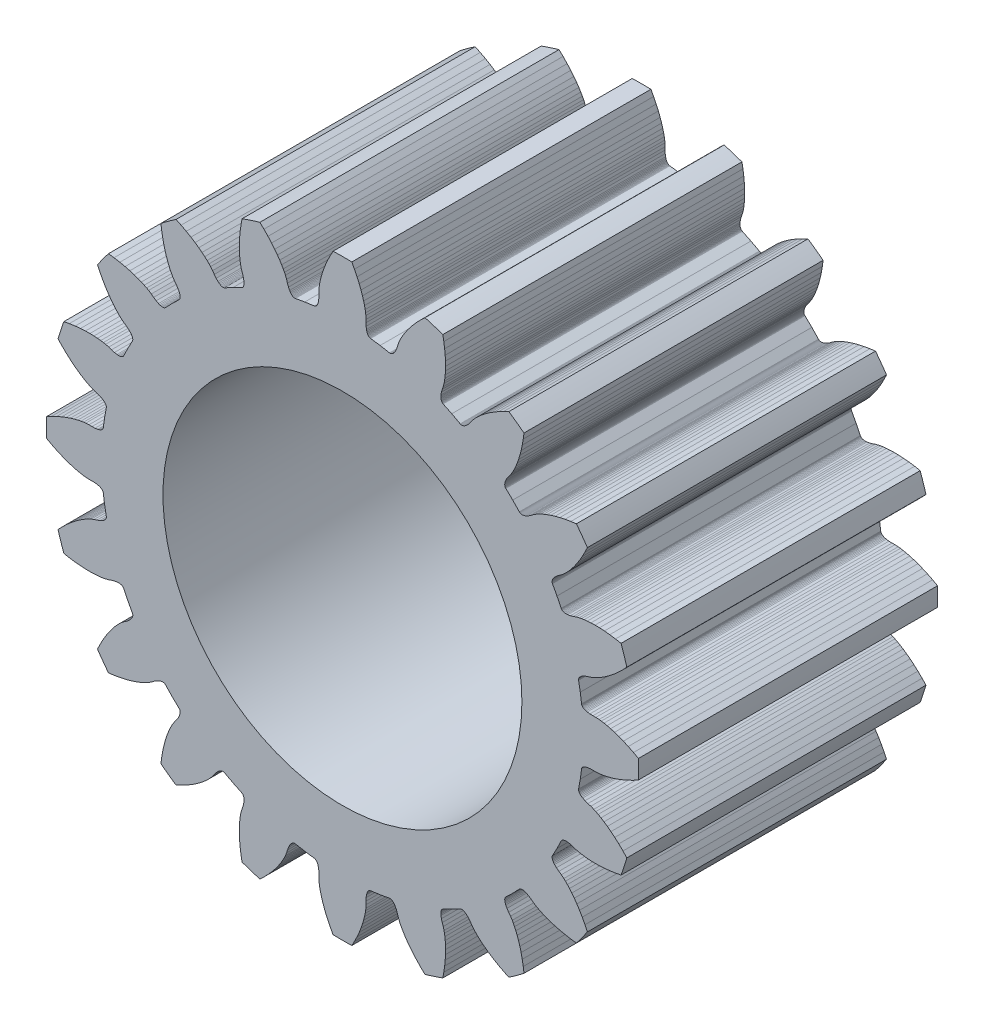
SolidWorks part; units mm, degrees
ref_plane "Front Plane" through (0, 0, 0) normal (0, 0, 1) x (1, 0, 0)
ref_plane "Top Plane" through (0, 0, 0) normal (0, 1, 0) x (1, 0, 0)
ref_plane "Right Plane" through (0, 0, 0) normal (1, 0, 0) x (0, 0, -1)
sketch "Model" plane through (0, 0, 0) normal (0, 0, 1) x (1, 0, 0)
  line L0 (9.378, 2.6243) -> (9.238, 2.4883)
  line L1 (9.238, 2.4883) -> (9.1039, 2.3686)
  line L2 (9.1039, 2.3686) -> (8.9764, 2.264)
  line L3 (8.9764, 2.264) -> (8.8564, 2.1736)
  line L4 (8.8564, 2.1736) -> (8.7443, 2.0963)
  line L5 (8.7443, 2.0963) -> (8.6424, 2.0323)
  line L6 (8.6424, 2.0323) -> (8.5499, 1.9794)
  line L7 (8.5499, 1.9794) -> (8.47, 1.938)
  line L8 (8.47, 1.938) -> (8.4018, 1.9062)
  line L9 (8.4018, 1.9062) -> (8.302, 1.8667)
  line L10 (8.302, 1.8667) -> (8.2067, 1.8384)
  line L11 (8.2067, 1.8384) -> (8.1107, 1.8037)
  line L12 (8.1107, 1.8037) -> (8.032, 1.7648)
  line L13 (8.032, 1.7648) -> (7.9992, 1.7442)
  line L14 (7.9992, 1.7442) -> (7.9707, 1.7231)
  line L15 (7.9707, 1.7231) -> (7.9467, 1.7016)
  line L16 (7.9467, 1.7016) -> (7.9271, 1.68)
  line L17 (7.9271, 1.68) -> (7.9118, 1.6584)
  line L18 (7.9118, 1.6584) -> (7.9009, 1.637)
  line L19 (7.9009, 1.637) -> (7.8944, 1.6159)
  line L20 (7.8944, 1.6159) -> (7.8922, 1.5954)
  line L21 (7.8922, 1.5954) -> (7.8943, 1.5756)
  line L22 (7.8943, 1.5756) -> (7.9509, 1.2593)
  line L23 (7.9509, 1.2593) -> (7.9948, 0.941)
  line L24 (7.9948, 0.941) -> (7.9989, 0.9215)
  line L25 (7.9989, 0.9215) -> (8.0074, 0.9027)
  line L26 (8.0074, 0.9027) -> (8.0201, 0.8846)
  line L27 (8.0201, 0.8846) -> (8.0371, 0.8676)
  line L28 (8.0371, 0.8676) -> (8.0583, 0.8518)
  line L29 (8.0583, 0.8518) -> (8.0836, 0.8373)
  line L30 (8.0836, 0.8373) -> (8.1131, 0.8243)
  line L31 (8.1131, 0.8243) -> (8.1466, 0.8131)
  line L32 (8.1466, 0.8131) -> (8.1842, 0.8036)
  line L33 (8.1842, 0.8036) -> (8.2711, 0.7909)
  line L34 (8.2711, 0.7909) -> (8.3731, 0.7876)
  line L35 (8.3731, 0.7876) -> (8.4726, 0.7901)
  line L36 (8.4726, 0.7901) -> (8.5797, 0.7834)
  line L37 (8.5797, 0.7834) -> (8.6544, 0.7742)
  line L38 (8.6544, 0.7742) -> (8.7431, 0.7596)
  line L39 (8.7431, 0.7596) -> (8.8474, 0.7378)
  line L40 (8.8474, 0.7378) -> (8.9641, 0.7084)
  line L41 (8.9641, 0.7084) -> (9.0946, 0.6696)
  line L42 (9.0946, 0.6696) -> (9.2367, 0.6207)
  line L43 (9.2367, 0.6207) -> (9.3903, 0.5606)
  line L44 (9.3903, 0.5606) -> (9.5547, 0.4882)
  line L45 (9.5547, 0.4882) -> (9.73, 0.4021)
  line L46 (9.73, 0.4021) -> (9.8951, 0.3125)
  line L47 (9.8951, -0.3125) -> (9.73, -0.4021)
  line L48 (9.73, -0.4021) -> (9.5547, -0.4882)
  line L49 (9.5547, -0.4882) -> (9.3903, -0.5606)
  line L50 (9.3903, -0.5606) -> (9.2367, -0.6207)
  line L51 (9.2367, -0.6207) -> (9.0946, -0.6696)
  line L52 (9.0946, -0.6696) -> (8.9641, -0.7084)
  line L53 (8.9641, -0.7084) -> (8.8474, -0.7378)
  line L54 (8.8474, -0.7378) -> (8.7431, -0.7596)
  line L55 (8.7431, -0.7596) -> (8.6544, -0.7742)
  line L56 (8.6544, -0.7742) -> (8.5797, -0.7834)
  line L57 (8.5797, -0.7834) -> (8.4726, -0.7901)
  line L58 (8.4726, -0.7901) -> (8.3731, -0.7876)
  line L59 (8.3731, -0.7876) -> (8.2711, -0.7909)
  line L60 (8.2711, -0.7909) -> (8.1842, -0.8036)
  line L61 (8.1842, -0.8036) -> (8.1466, -0.8131)
  line L62 (8.1466, -0.8131) -> (8.1131, -0.8243)
  line L63 (8.1131, -0.8243) -> (8.0836, -0.8373)
  line L64 (8.0836, -0.8373) -> (8.0583, -0.8518)
  line L65 (8.0583, -0.8518) -> (8.0371, -0.8676)
  line L66 (8.0371, -0.8676) -> (8.0201, -0.8846)
  line L67 (8.0201, -0.8846) -> (8.0074, -0.9027)
  line L68 (8.0074, -0.9027) -> (7.9989, -0.9215)
  line L69 (7.9989, -0.9215) -> (7.9948, -0.941)
  line L70 (7.9948, -0.941) -> (7.9509, -1.2593)
  line L71 (7.9509, -1.2593) -> (7.8943, -1.5756)
  line L72 (7.8943, -1.5756) -> (7.8922, -1.5954)
  line L73 (7.8922, -1.5954) -> (7.8944, -1.6159)
  line L74 (7.8944, -1.6159) -> (7.9009, -1.637)
  line L75 (7.9009, -1.637) -> (7.9118, -1.6584)
  line L76 (7.9118, -1.6584) -> (7.9271, -1.68)
  line L77 (7.9271, -1.68) -> (7.9467, -1.7016)
  line L78 (7.9467, -1.7016) -> (7.9707, -1.7231)
  line L79 (7.9707, -1.7231) -> (7.9992, -1.7442)
  line L80 (7.9992, -1.7442) -> (8.032, -1.7648)
  line L81 (8.032, -1.7648) -> (8.1107, -1.8037)
  line L82 (8.1107, -1.8037) -> (8.2067, -1.8384)
  line L83 (8.2067, -1.8384) -> (8.302, -1.8667)
  line L84 (8.302, -1.8667) -> (8.4018, -1.9062)
  line L85 (8.4018, -1.9062) -> (8.47, -1.938)
  line L86 (8.47, -1.938) -> (8.5499, -1.9794)
  line L87 (8.5499, -1.9794) -> (8.6424, -2.0323)
  line L88 (8.6424, -2.0323) -> (8.7443, -2.0963)
  line L89 (8.7443, -2.0963) -> (8.8564, -2.1736)
  line L90 (8.8564, -2.1736) -> (8.9764, -2.264)
  line L91 (8.9764, -2.264) -> (9.1039, -2.3686)
  line L92 (9.1039, -2.3686) -> (9.238, -2.4883)
  line L93 (9.238, -2.4883) -> (9.378, -2.6243)
  line L94 (9.378, -2.6243) -> (9.5073, -2.7605)
  line L95 (9.3142, -3.355) -> (9.1295, -3.3891)
  line L96 (9.1295, -3.3891) -> (8.9362, -3.4169)
  line L97 (8.9362, -3.4169) -> (8.7574, -3.4349)
  line L98 (8.7574, -3.4349) -> (8.5928, -3.4446)
  line L99 (8.5928, -3.4446) -> (8.4425, -3.4472)
  line L100 (8.4425, -3.4472) -> (8.3065, -3.4438)
  line L101 (8.3065, -3.4438) -> (8.1864, -3.4357)
  line L102 (8.1864, -3.4357) -> (8.0805, -3.4242)
  line L103 (8.0805, -3.4242) -> (7.9915, -3.4107)
  line L104 (7.9915, -3.4107) -> (7.9177, -3.3963)
  line L105 (7.9177, -3.3963) -> (7.8137, -3.3696)
  line L106 (7.8137, -3.3696) -> (7.7199, -3.3364)
  line L107 (7.7199, -3.3364) -> (7.6218, -3.3081)
  line L108 (7.6218, -3.3081) -> (7.5353, -3.2933)
  line L109 (7.5353, -3.2933) -> (7.4967, -3.2907)
  line L110 (7.4967, -3.2907) -> (7.4613, -3.2911)
  line L111 (7.4613, -3.2911) -> (7.4292, -3.2943)
  line L112 (7.4292, -3.2943) -> (7.4006, -3.3002)
  line L113 (7.4006, -3.3002) -> (7.3756, -3.3088)
  line L114 (7.3756, -3.3088) -> (7.3542, -3.3197)
  line L115 (7.3542, -3.3197) -> (7.3365, -3.3329)
  line L116 (7.3365, -3.3329) -> (7.3227, -3.3482)
  line L117 (7.3227, -3.3482) -> (7.3127, -3.3655)
  line L118 (7.3127, -3.3655) -> (7.1726, -3.6546)
  line L119 (7.1726, -3.6546) -> (7.0211, -3.9379)
  line L120 (7.0211, -3.9379) -> (7.0129, -3.9561)
  line L121 (7.0129, -3.9561) -> (7.0087, -3.9764)
  line L122 (7.0087, -3.9764) -> (7.0084, -3.9984)
  line L123 (7.0084, -3.9984) -> (7.0121, -4.0221)
  line L124 (7.0121, -4.0221) -> (7.0199, -4.0474)
  line L125 (7.0199, -4.0474) -> (7.0319, -4.074)
  line L126 (7.0319, -4.074) -> (7.0482, -4.1018)
  line L127 (7.0482, -4.1018) -> (7.0687, -4.1307)
  line L128 (7.0687, -4.1307) -> (7.0935, -4.1604)
  line L129 (7.0935, -4.1604) -> (7.1563, -4.2217)
  line L130 (7.1563, -4.2217) -> (7.2369, -4.2845)
  line L131 (7.2369, -4.2845) -> (7.3189, -4.3408)
  line L132 (7.3189, -4.3408) -> (7.4016, -4.4092)
  line L133 (7.4016, -4.4092) -> (7.4566, -4.4606)
  line L134 (7.4566, -4.4606) -> (7.5198, -4.5246)
  line L135 (7.5198, -4.5246) -> (7.5914, -4.6035)
  line L136 (7.5914, -4.6035) -> (7.6685, -4.6959)
  line L137 (7.6685, -4.6959) -> (7.7512, -4.804)
  line L138 (7.7512, -4.804) -> (7.8375, -4.927)
  line L139 (7.8375, -4.927) -> (7.9264, -5.0659)
  line L140 (7.9264, -5.0659) -> (8.0169, -5.2212)
  line L141 (8.0169, -5.2212) -> (8.1081, -5.3938)
  line L142 (8.1081, -5.3938) -> (8.189, -5.5633)
  line L143 (7.8216, -6.069) -> (7.6354, -6.0444)
  line L144 (7.6354, -6.0444) -> (7.443, -6.0111)
  line L145 (7.443, -6.0111) -> (7.2674, -5.973)
  line L146 (7.2674, -5.973) -> (7.1078, -5.9313)
  line L147 (7.1078, -5.9313) -> (6.9641, -5.8874)
  line L148 (6.9641, -5.8874) -> (6.8357, -5.8421)
  line L149 (6.8357, -5.8421) -> (6.724, -5.7973)
  line L150 (6.724, -5.7973) -> (6.6269, -5.7536)
  line L151 (6.6269, -5.7536) -> (6.5465, -5.7133)
  line L152 (6.5465, -5.7133) -> (6.4806, -5.6768)
  line L153 (6.4806, -5.6768) -> (6.39, -5.6193)
  line L154 (6.39, -5.6193) -> (6.3111, -5.5587)
  line L155 (6.3111, -5.5587) -> (6.2265, -5.5015)
  line L156 (6.2265, -5.5015) -> (6.1488, -5.4607)
  line L157 (6.1488, -5.4607) -> (6.1129, -5.4463)
  line L158 (6.1129, -5.4463) -> (6.0791, -5.4357)
  line L159 (6.0791, -5.4357) -> (6.0476, -5.4288)
  line L160 (6.0476, -5.4288) -> (6.0186, -5.4256)
  line L161 (6.0186, -5.4256) -> (5.9922, -5.426)
  line L162 (5.9922, -5.426) -> (5.9684, -5.4298)
  line L163 (5.9684, -5.4298) -> (5.9475, -5.4369)
  line L164 (5.9475, -5.4369) -> (5.9296, -5.4472)
  line L165 (5.9296, -5.4472) -> (5.9148, -5.4606)
  line L166 (5.9148, -5.4606) -> (5.6922, -5.6922)
  line L167 (5.6922, -5.6922) -> (5.4606, -5.9148)
  line L168 (5.4606, -5.9148) -> (5.4472, -5.9296)
  line L169 (5.4472, -5.9296) -> (5.4369, -5.9475)
  line L170 (5.4369, -5.9475) -> (5.4298, -5.9684)
  line L171 (5.4298, -5.9684) -> (5.426, -5.9922)
  line L172 (5.426, -5.9922) -> (5.4256, -6.0186)
  line L173 (5.4256, -6.0186) -> (5.4288, -6.0476)
  line L174 (5.4288, -6.0476) -> (5.4357, -6.0791)
  line L175 (5.4357, -6.0791) -> (5.4463, -6.1129)
  line L176 (5.4463, -6.1129) -> (5.4607, -6.1488)
  line L177 (5.4607, -6.1488) -> (5.5015, -6.2265)
  line L178 (5.5015, -6.2265) -> (5.5587, -6.3111)
  line L179 (5.5587, -6.3111) -> (5.6193, -6.39)
  line L180 (5.6193, -6.39) -> (5.6768, -6.4806)
  line L181 (5.6768, -6.4806) -> (5.7133, -6.5465)
  line L182 (5.7133, -6.5465) -> (5.7536, -6.6269)
  line L183 (5.7536, -6.6269) -> (5.7973, -6.724)
  line L184 (5.7973, -6.724) -> (5.8421, -6.8357)
  line L185 (5.8421, -6.8357) -> (5.8874, -6.9641)
  line L186 (5.8874, -6.9641) -> (5.9313, -7.1078)
  line L187 (5.9313, -7.1078) -> (5.973, -7.2674)
  line L188 (5.973, -7.2674) -> (6.0111, -7.443)
  line L189 (6.0111, -7.443) -> (6.0444, -7.6354)
  line L190 (6.0444, -7.6354) -> (6.069, -7.8216)
  line L191 (5.5633, -8.189) -> (5.3938, -8.1081)
  line L192 (5.3938, -8.1081) -> (5.2212, -8.0169)
  line L193 (5.2212, -8.0169) -> (5.0659, -7.9264)
  line L194 (5.0659, -7.9264) -> (4.927, -7.8375)
  line L195 (4.927, -7.8375) -> (4.804, -7.7512)
  line L196 (4.804, -7.7512) -> (4.6959, -7.6685)
  line L197 (4.6959, -7.6685) -> (4.6035, -7.5914)
  line L198 (4.6035, -7.5914) -> (4.5246, -7.5198)
  line L199 (4.5246, -7.5198) -> (4.4606, -7.4566)
  line L200 (4.4606, -7.4566) -> (4.4092, -7.4016)
  line L201 (4.4092, -7.4016) -> (4.3408, -7.3189)
  line L202 (4.3408, -7.3189) -> (4.2845, -7.2369)
  line L203 (4.2845, -7.2369) -> (4.2217, -7.1563)
  line L204 (4.2217, -7.1563) -> (4.1604, -7.0935)
  line L205 (4.1604, -7.0935) -> (4.1307, -7.0687)
  line L206 (4.1307, -7.0687) -> (4.1018, -7.0482)
  line L207 (4.1018, -7.0482) -> (4.074, -7.0319)
  line L208 (4.074, -7.0319) -> (4.0474, -7.0199)
  line L209 (4.0474, -7.0199) -> (4.0221, -7.0121)
  line L210 (4.0221, -7.0121) -> (3.9984, -7.0084)
  line L211 (3.9984, -7.0084) -> (3.9764, -7.0087)
  line L212 (3.9764, -7.0087) -> (3.9561, -7.0129)
  line L213 (3.9561, -7.0129) -> (3.9379, -7.0211)
  line L214 (3.9379, -7.0211) -> (3.6546, -7.1726)
  line L215 (3.6546, -7.1726) -> (3.3655, -7.3127)
  line L216 (3.3655, -7.3127) -> (3.3482, -7.3227)
  line L217 (3.3482, -7.3227) -> (3.3329, -7.3365)
  line L218 (3.3329, -7.3365) -> (3.3197, -7.3542)
  line L219 (3.3197, -7.3542) -> (3.3088, -7.3756)
  line L220 (3.3088, -7.3756) -> (3.3002, -7.4006)
  line L221 (3.3002, -7.4006) -> (3.2943, -7.4292)
  line L222 (3.2943, -7.4292) -> (3.2911, -7.4613)
  line L223 (3.2911, -7.4613) -> (3.2907, -7.4967)
  line L224 (3.2907, -7.4967) -> (3.2933, -7.5353)
  line L225 (3.2933, -7.5353) -> (3.3081, -7.6218)
  line L226 (3.3081, -7.6218) -> (3.3364, -7.7199)
  line L227 (3.3364, -7.7199) -> (3.3696, -7.8137)
  line L228 (3.3696, -7.8137) -> (3.3963, -7.9177)
  line L229 (3.3963, -7.9177) -> (3.4107, -7.9915)
  line L230 (3.4107, -7.9915) -> (3.4242, -8.0805)
  line L231 (3.4242, -8.0805) -> (3.4357, -8.1864)
  line L232 (3.4357, -8.1864) -> (3.4438, -8.3065)
  line L233 (3.4438, -8.3065) -> (3.4472, -8.4425)
  line L234 (3.4472, -8.4425) -> (3.4446, -8.5928)
  line L235 (3.4446, -8.5928) -> (3.4349, -8.7574)
  line L236 (3.4349, -8.7574) -> (3.4169, -8.9362)
  line L237 (3.4169, -8.9362) -> (3.3891, -9.1295)
  line L238 (3.3891, -9.1295) -> (3.355, -9.3142)
  line L239 (2.7605, -9.5073) -> (2.6243, -9.378)
  line L240 (2.6243, -9.378) -> (2.4883, -9.238)
  line L241 (2.4883, -9.238) -> (2.3686, -9.1039)
  line L242 (2.3686, -9.1039) -> (2.264, -8.9764)
  line L243 (2.264, -8.9764) -> (2.1736, -8.8564)
  line L244 (2.1736, -8.8564) -> (2.0963, -8.7443)
  line L245 (2.0963, -8.7443) -> (2.0323, -8.6424)
  line L246 (2.0323, -8.6424) -> (1.9794, -8.5499)
  line L247 (1.9794, -8.5499) -> (1.938, -8.47)
  line L248 (1.938, -8.47) -> (1.9062, -8.4018)
  line L249 (1.9062, -8.4018) -> (1.8667, -8.302)
  line L250 (1.8667, -8.302) -> (1.8384, -8.2067)
  line L251 (1.8384, -8.2067) -> (1.8037, -8.1107)
  line L252 (1.8037, -8.1107) -> (1.7648, -8.032)
  line L253 (1.7648, -8.032) -> (1.7442, -7.9992)
  line L254 (1.7442, -7.9992) -> (1.7231, -7.9707)
  line L255 (1.7231, -7.9707) -> (1.7016, -7.9467)
  line L256 (1.7016, -7.9467) -> (1.68, -7.9271)
  line L257 (1.68, -7.9271) -> (1.6584, -7.9118)
  line L258 (1.6584, -7.9118) -> (1.637, -7.9009)
  line L259 (1.637, -7.9009) -> (1.6159, -7.8944)
  line L260 (1.6159, -7.8944) -> (1.5954, -7.8922)
  line L261 (1.5954, -7.8922) -> (1.5756, -7.8943)
  line L262 (1.5756, -7.8943) -> (1.2593, -7.9509)
  line L263 (1.2593, -7.9509) -> (0.941, -7.9948)
  line L264 (0.941, -7.9948) -> (0.9215, -7.9989)
  line L265 (0.9215, -7.9989) -> (0.9027, -8.0074)
  line L266 (0.9027, -8.0074) -> (0.8846, -8.0201)
  line L267 (0.8846, -8.0201) -> (0.8676, -8.0371)
  line L268 (0.8676, -8.0371) -> (0.8518, -8.0583)
  line L269 (0.8518, -8.0583) -> (0.8373, -8.0836)
  line L270 (0.8373, -8.0836) -> (0.8243, -8.1131)
  line L271 (0.8243, -8.1131) -> (0.8131, -8.1466)
  line L272 (0.8131, -8.1466) -> (0.8036, -8.1842)
  line L273 (0.8036, -8.1842) -> (0.7909, -8.2711)
  line L274 (0.7909, -8.2711) -> (0.7876, -8.3731)
  line L275 (0.7876, -8.3731) -> (0.7901, -8.4726)
  line L276 (0.7901, -8.4726) -> (0.7834, -8.5797)
  line L277 (0.7834, -8.5797) -> (0.7742, -8.6544)
  line L278 (0.7742, -8.6544) -> (0.7596, -8.7431)
  line L279 (0.7596, -8.7431) -> (0.7378, -8.8474)
  line L280 (0.7378, -8.8474) -> (0.7084, -8.9641)
  line L281 (0.7084, -8.9641) -> (0.6696, -9.0946)
  line L282 (0.6696, -9.0946) -> (0.6207, -9.2367)
  line L283 (0.6207, -9.2367) -> (0.5606, -9.3903)
  line L284 (0.5606, -9.3903) -> (0.4882, -9.5547)
  line L285 (0.4882, -9.5547) -> (0.4021, -9.73)
  line L286 (0.4021, -9.73) -> (0.3125, -9.8951)
  line L287 (-0.3125, -9.8951) -> (-0.4021, -9.73)
  line L288 (-0.4021, -9.73) -> (-0.4882, -9.5547)
  line L289 (-0.4882, -9.5547) -> (-0.5606, -9.3903)
  line L290 (-0.5606, -9.3903) -> (-0.6207, -9.2367)
  line L291 (-0.6207, -9.2367) -> (-0.6696, -9.0946)
  line L292 (-0.6696, -9.0946) -> (-0.7084, -8.9641)
  line L293 (-0.7084, -8.9641) -> (-0.7378, -8.8474)
  line L294 (-0.7378, -8.8474) -> (-0.7596, -8.7431)
  line L295 (-0.7596, -8.7431) -> (-0.7742, -8.6544)
  line L296 (-0.7742, -8.6544) -> (-0.7834, -8.5797)
  line L297 (-0.7834, -8.5797) -> (-0.7901, -8.4726)
  line L298 (-0.7901, -8.4726) -> (-0.7876, -8.3731)
  line L299 (-0.7876, -8.3731) -> (-0.7909, -8.2711)
  line L300 (-0.7909, -8.2711) -> (-0.8036, -8.1842)
  line L301 (-0.8036, -8.1842) -> (-0.8131, -8.1466)
  line L302 (-0.8131, -8.1466) -> (-0.8243, -8.1131)
  line L303 (-0.8243, -8.1131) -> (-0.8373, -8.0836)
  line L304 (-0.8373, -8.0836) -> (-0.8518, -8.0583)
  line L305 (-0.8518, -8.0583) -> (-0.8676, -8.0371)
  line L306 (-0.8676, -8.0371) -> (-0.8846, -8.0201)
  line L307 (-0.8846, -8.0201) -> (-0.9027, -8.0074)
  line L308 (-0.9027, -8.0074) -> (-0.9215, -7.9989)
  line L309 (-0.9215, -7.9989) -> (-0.941, -7.9948)
  line L310 (-0.941, -7.9948) -> (-1.2593, -7.9509)
  line L311 (-1.2593, -7.9509) -> (-1.5756, -7.8943)
  line L312 (-1.5756, -7.8943) -> (-1.5954, -7.8922)
  line L313 (-1.5954, -7.8922) -> (-1.6159, -7.8944)
  line L314 (-1.6159, -7.8944) -> (-1.637, -7.9009)
  line L315 (-1.637, -7.9009) -> (-1.6584, -7.9118)
  line L316 (-1.6584, -7.9118) -> (-1.68, -7.9271)
  line L317 (-1.68, -7.9271) -> (-1.7016, -7.9467)
  line L318 (-1.7016, -7.9467) -> (-1.7231, -7.9707)
  line L319 (-1.7231, -7.9707) -> (-1.7442, -7.9992)
  line L320 (-1.7442, -7.9992) -> (-1.7648, -8.032)
  line L321 (-1.7648, -8.032) -> (-1.8037, -8.1107)
  line L322 (-1.8037, -8.1107) -> (-1.8384, -8.2067)
  line L323 (-1.8384, -8.2067) -> (-1.8667, -8.302)
  line L324 (-1.8667, -8.302) -> (-1.9062, -8.4018)
  line L325 (-1.9062, -8.4018) -> (-1.938, -8.47)
  line L326 (-1.938, -8.47) -> (-1.9794, -8.5499)
  line L327 (-1.9794, -8.5499) -> (-2.0323, -8.6424)
  line L328 (-2.0323, -8.6424) -> (-2.0963, -8.7443)
  line L329 (-2.0963, -8.7443) -> (-2.1736, -8.8564)
  line L330 (-2.1736, -8.8564) -> (-2.264, -8.9764)
  line L331 (-2.264, -8.9764) -> (-2.3686, -9.1039)
  line L332 (-2.3686, -9.1039) -> (-2.4883, -9.238)
  line L333 (-2.4883, -9.238) -> (-2.6243, -9.378)
  line L334 (-2.6243, -9.378) -> (-2.7605, -9.5073)
  line L335 (-3.355, -9.3142) -> (-3.3891, -9.1295)
  line L336 (-3.3891, -9.1295) -> (-3.4169, -8.9362)
  line L337 (-3.4169, -8.9362) -> (-3.4349, -8.7574)
  line L338 (-3.4349, -8.7574) -> (-3.4446, -8.5928)
  line L339 (-3.4446, -8.5928) -> (-3.4472, -8.4425)
  line L340 (-3.4472, -8.4425) -> (-3.4438, -8.3065)
  line L341 (-3.4438, -8.3065) -> (-3.4357, -8.1864)
  line L342 (-3.4357, -8.1864) -> (-3.4242, -8.0805)
  line L343 (-3.4242, -8.0805) -> (-3.4107, -7.9915)
  line L344 (-3.4107, -7.9915) -> (-3.3963, -7.9177)
  line L345 (-3.3963, -7.9177) -> (-3.3696, -7.8137)
  line L346 (-3.3696, -7.8137) -> (-3.3364, -7.7199)
  line L347 (-3.3364, -7.7199) -> (-3.3081, -7.6218)
  line L348 (-3.3081, -7.6218) -> (-3.2933, -7.5353)
  line L349 (-3.2933, -7.5353) -> (-3.2907, -7.4967)
  line L350 (-3.2907, -7.4967) -> (-3.2911, -7.4613)
  line L351 (-3.2911, -7.4613) -> (-3.2943, -7.4292)
  line L352 (-3.2943, -7.4292) -> (-3.3002, -7.4006)
  line L353 (-3.3002, -7.4006) -> (-3.3088, -7.3756)
  line L354 (-3.3088, -7.3756) -> (-3.3197, -7.3542)
  line L355 (-3.3197, -7.3542) -> (-3.3329, -7.3365)
  line L356 (-3.3329, -7.3365) -> (-3.3482, -7.3227)
  line L357 (-3.3482, -7.3227) -> (-3.3655, -7.3127)
  line L358 (-3.3655, -7.3127) -> (-3.6546, -7.1726)
  line L359 (-3.6546, -7.1726) -> (-3.9379, -7.0211)
  line L360 (-3.9379, -7.0211) -> (-3.9561, -7.0129)
  line L361 (-3.9561, -7.0129) -> (-3.9764, -7.0087)
  line L362 (-3.9764, -7.0087) -> (-3.9984, -7.0084)
  line L363 (-3.9984, -7.0084) -> (-4.0221, -7.0121)
  line L364 (-4.0221, -7.0121) -> (-4.0474, -7.0199)
  line L365 (-4.0474, -7.0199) -> (-4.074, -7.0319)
  line L366 (-4.074, -7.0319) -> (-4.1018, -7.0482)
  line L367 (-4.1018, -7.0482) -> (-4.1307, -7.0687)
  line L368 (-4.1307, -7.0687) -> (-4.1604, -7.0935)
  line L369 (-4.1604, -7.0935) -> (-4.2217, -7.1563)
  line L370 (-4.2217, -7.1563) -> (-4.2845, -7.2369)
  line L371 (-4.2845, -7.2369) -> (-4.3408, -7.3189)
  line L372 (-4.3408, -7.3189) -> (-4.4092, -7.4016)
  line L373 (-4.4092, -7.4016) -> (-4.4606, -7.4566)
  line L374 (-4.4606, -7.4566) -> (-4.5246, -7.5198)
  line L375 (-4.5246, -7.5198) -> (-4.6035, -7.5914)
  line L376 (-4.6035, -7.5914) -> (-4.6959, -7.6685)
  line L377 (-4.6959, -7.6685) -> (-4.804, -7.7512)
  line L378 (-4.804, -7.7512) -> (-4.927, -7.8375)
  line L379 (-4.927, -7.8375) -> (-5.0659, -7.9264)
  line L380 (-5.0659, -7.9264) -> (-5.2212, -8.0169)
  line L381 (-5.2212, -8.0169) -> (-5.3938, -8.1081)
  line L382 (-5.3938, -8.1081) -> (-5.5633, -8.189)
  line L383 (-6.069, -7.8216) -> (-6.0444, -7.6354)
  line L384 (-6.0444, -7.6354) -> (-6.0111, -7.443)
  line L385 (-6.0111, -7.443) -> (-5.973, -7.2674)
  line L386 (-5.973, -7.2674) -> (-5.9313, -7.1078)
  line L387 (-5.9313, -7.1078) -> (-5.8874, -6.9641)
  line L388 (-5.8874, -6.9641) -> (-5.8421, -6.8357)
  line L389 (-5.8421, -6.8357) -> (-5.7973, -6.724)
  line L390 (-5.7973, -6.724) -> (-5.7536, -6.6269)
  line L391 (-5.7536, -6.6269) -> (-5.7133, -6.5465)
  line L392 (-5.7133, -6.5465) -> (-5.6768, -6.4806)
  line L393 (-5.6768, -6.4806) -> (-5.6193, -6.39)
  line L394 (-5.6193, -6.39) -> (-5.5587, -6.3111)
  line L395 (-5.5587, -6.3111) -> (-5.5015, -6.2265)
  line L396 (-5.5015, -6.2265) -> (-5.4607, -6.1488)
  line L397 (-5.4607, -6.1488) -> (-5.4463, -6.1129)
  line L398 (-5.4463, -6.1129) -> (-5.4357, -6.0791)
  line L399 (-5.4357, -6.0791) -> (-5.4288, -6.0476)
  line L400 (-5.4288, -6.0476) -> (-5.4256, -6.0186)
  line L401 (-5.4256, -6.0186) -> (-5.426, -5.9922)
  line L402 (-5.426, -5.9922) -> (-5.4298, -5.9684)
  line L403 (-5.4298, -5.9684) -> (-5.4369, -5.9475)
  line L404 (-5.4369, -5.9475) -> (-5.4472, -5.9296)
  line L405 (-5.4472, -5.9296) -> (-5.4606, -5.9148)
  line L406 (-5.4606, -5.9148) -> (-5.6922, -5.6922)
  line L407 (-5.6922, -5.6922) -> (-5.9148, -5.4606)
  line L408 (-5.9148, -5.4606) -> (-5.9296, -5.4472)
  line L409 (-5.9296, -5.4472) -> (-5.9475, -5.4369)
  line L410 (-5.9475, -5.4369) -> (-5.9684, -5.4298)
  line L411 (-5.9684, -5.4298) -> (-5.9922, -5.426)
  line L412 (-5.9922, -5.426) -> (-6.0186, -5.4256)
  line L413 (-6.0186, -5.4256) -> (-6.0476, -5.4288)
  line L414 (-6.0476, -5.4288) -> (-6.0791, -5.4357)
  line L415 (-6.0791, -5.4357) -> (-6.1129, -5.4463)
  line L416 (-6.1129, -5.4463) -> (-6.1488, -5.4607)
  line L417 (-6.1488, -5.4607) -> (-6.2265, -5.5015)
  line L418 (-6.2265, -5.5015) -> (-6.3111, -5.5587)
  line L419 (-6.3111, -5.5587) -> (-6.39, -5.6193)
  line L420 (-6.39, -5.6193) -> (-6.4806, -5.6768)
  line L421 (-6.4806, -5.6768) -> (-6.5465, -5.7133)
  line L422 (-6.5465, -5.7133) -> (-6.6269, -5.7536)
  line L423 (-6.6269, -5.7536) -> (-6.724, -5.7973)
  line L424 (-6.724, -5.7973) -> (-6.8357, -5.8421)
  line L425 (-6.8357, -5.8421) -> (-6.9641, -5.8874)
  line L426 (-6.9641, -5.8874) -> (-7.1078, -5.9313)
  line L427 (-7.1078, -5.9313) -> (-7.2674, -5.973)
  line L428 (-7.2674, -5.973) -> (-7.443, -6.0111)
  line L429 (-7.443, -6.0111) -> (-7.6354, -6.0444)
  line L430 (-7.6354, -6.0444) -> (-7.8216, -6.069)
  line L431 (-8.189, -5.5633) -> (-8.1081, -5.3938)
  line L432 (-8.1081, -5.3938) -> (-8.0169, -5.2212)
  line L433 (-8.0169, -5.2212) -> (-7.9264, -5.0659)
  line L434 (-7.9264, -5.0659) -> (-7.8375, -4.927)
  line L435 (-7.8375, -4.927) -> (-7.7512, -4.804)
  line L436 (-7.7512, -4.804) -> (-7.6685, -4.6959)
  line L437 (-7.6685, -4.6959) -> (-7.5914, -4.6035)
  line L438 (-7.5914, -4.6035) -> (-7.5198, -4.5246)
  line L439 (-7.5198, -4.5246) -> (-7.4566, -4.4606)
  line L440 (-7.4566, -4.4606) -> (-7.4016, -4.4092)
  line L441 (-7.4016, -4.4092) -> (-7.3189, -4.3408)
  line L442 (-7.3189, -4.3408) -> (-7.2369, -4.2845)
  line L443 (-7.2369, -4.2845) -> (-7.1563, -4.2217)
  line L444 (-7.1563, -4.2217) -> (-7.0935, -4.1604)
  line L445 (-7.0935, -4.1604) -> (-7.0687, -4.1307)
  line L446 (-7.0687, -4.1307) -> (-7.0482, -4.1018)
  line L447 (-7.0482, -4.1018) -> (-7.0319, -4.074)
  line L448 (-7.0319, -4.074) -> (-7.0199, -4.0474)
  line L449 (-7.0199, -4.0474) -> (-7.0121, -4.0221)
  line L450 (-7.0121, -4.0221) -> (-7.0084, -3.9984)
  line L451 (-7.0084, -3.9984) -> (-7.0087, -3.9764)
  line L452 (-7.0087, -3.9764) -> (-7.0129, -3.9561)
  line L453 (-7.0129, -3.9561) -> (-7.0211, -3.9379)
  line L454 (-7.0211, -3.9379) -> (-7.1726, -3.6546)
  line L455 (-7.1726, -3.6546) -> (-7.3127, -3.3655)
  line L456 (-7.3127, -3.3655) -> (-7.3227, -3.3482)
  line L457 (-7.3227, -3.3482) -> (-7.3365, -3.3329)
  line L458 (-7.3365, -3.3329) -> (-7.3542, -3.3197)
  line L459 (-7.3542, -3.3197) -> (-7.3756, -3.3088)
  line L460 (-7.3756, -3.3088) -> (-7.4006, -3.3002)
  line L461 (-7.4006, -3.3002) -> (-7.4292, -3.2943)
  line L462 (-7.4292, -3.2943) -> (-7.4613, -3.2911)
  line L463 (-7.4613, -3.2911) -> (-7.4967, -3.2907)
  line L464 (-7.4967, -3.2907) -> (-7.5353, -3.2933)
  line L465 (-7.5353, -3.2933) -> (-7.6218, -3.3081)
  line L466 (-7.6218, -3.3081) -> (-7.7199, -3.3364)
  line L467 (-7.7199, -3.3364) -> (-7.8137, -3.3696)
  line L468 (-7.8137, -3.3696) -> (-7.9177, -3.3963)
  line L469 (-7.9177, -3.3963) -> (-7.9915, -3.4107)
  line L470 (-7.9915, -3.4107) -> (-8.0805, -3.4242)
  line L471 (-8.0805, -3.4242) -> (-8.1864, -3.4357)
  line L472 (-8.1864, -3.4357) -> (-8.3065, -3.4438)
  line L473 (-8.3065, -3.4438) -> (-8.4425, -3.4472)
  line L474 (-8.4425, -3.4472) -> (-8.5928, -3.4446)
  line L475 (-8.5928, -3.4446) -> (-8.7574, -3.4349)
  line L476 (-8.7574, -3.4349) -> (-8.9362, -3.4169)
  line L477 (-8.9362, -3.4169) -> (-9.1295, -3.3891)
  line L478 (-9.1295, -3.3891) -> (-9.3142, -3.355)
  line L479 (-9.5073, -2.7605) -> (-9.378, -2.6243)
  line L480 (-9.378, -2.6243) -> (-9.238, -2.4883)
  line L481 (-9.238, -2.4883) -> (-9.1039, -2.3686)
  line L482 (-9.1039, -2.3686) -> (-8.9764, -2.264)
  line L483 (-8.9764, -2.264) -> (-8.8564, -2.1736)
  line L484 (-8.8564, -2.1736) -> (-8.7443, -2.0963)
  line L485 (-8.7443, -2.0963) -> (-8.6424, -2.0323)
  line L486 (-8.6424, -2.0323) -> (-8.5499, -1.9794)
  line L487 (-8.5499, -1.9794) -> (-8.47, -1.938)
  line L488 (-8.47, -1.938) -> (-8.4018, -1.9062)
  line L489 (-8.4018, -1.9062) -> (-8.302, -1.8667)
  line L490 (-8.302, -1.8667) -> (-8.2067, -1.8384)
  line L491 (-8.2067, -1.8384) -> (-8.1107, -1.8037)
  line L492 (-8.1107, -1.8037) -> (-8.032, -1.7648)
  line L493 (-8.032, -1.7648) -> (-7.9992, -1.7442)
  line L494 (-7.9992, -1.7442) -> (-7.9707, -1.7231)
  line L495 (-7.9707, -1.7231) -> (-7.9467, -1.7016)
  line L496 (-7.9467, -1.7016) -> (-7.9271, -1.68)
  line L497 (-7.9271, -1.68) -> (-7.9118, -1.6584)
  line L498 (-7.9118, -1.6584) -> (-7.9009, -1.637)
  line L499 (-7.9009, -1.637) -> (-7.8944, -1.6159)
  line L500 (-7.8944, -1.6159) -> (-7.8922, -1.5954)
  line L501 (-7.8922, -1.5954) -> (-7.8943, -1.5756)
  line L502 (-7.8943, -1.5756) -> (-7.9509, -1.2593)
  line L503 (-7.9509, -1.2593) -> (-7.9948, -0.941)
  line L504 (-7.9948, -0.941) -> (-7.9989, -0.9215)
  line L505 (-7.9989, -0.9215) -> (-8.0074, -0.9027)
  line L506 (-8.0074, -0.9027) -> (-8.0201, -0.8846)
  line L507 (-8.0201, -0.8846) -> (-8.0371, -0.8676)
  line L508 (-8.0371, -0.8676) -> (-8.0583, -0.8518)
  line L509 (-8.0583, -0.8518) -> (-8.0836, -0.8373)
  line L510 (-8.0836, -0.8373) -> (-8.1131, -0.8243)
  line L511 (-8.1131, -0.8243) -> (-8.1466, -0.8131)
  line L512 (-8.1466, -0.8131) -> (-8.1842, -0.8036)
  line L513 (-8.1842, -0.8036) -> (-8.2711, -0.7909)
  line L514 (-8.2711, -0.7909) -> (-8.3731, -0.7876)
  line L515 (-8.3731, -0.7876) -> (-8.4726, -0.7901)
  line L516 (-8.4726, -0.7901) -> (-8.5797, -0.7834)
  line L517 (-8.5797, -0.7834) -> (-8.6544, -0.7742)
  line L518 (-8.6544, -0.7742) -> (-8.7431, -0.7596)
  line L519 (-8.7431, -0.7596) -> (-8.8474, -0.7378)
  line L520 (-8.8474, -0.7378) -> (-8.9641, -0.7084)
  line L521 (-8.9641, -0.7084) -> (-9.0946, -0.6696)
  line L522 (-9.0946, -0.6696) -> (-9.2367, -0.6207)
  line L523 (-9.2367, -0.6207) -> (-9.3903, -0.5606)
  line L524 (-9.3903, -0.5606) -> (-9.5547, -0.4882)
  line L525 (-9.5547, -0.4882) -> (-9.73, -0.4021)
  line L526 (-9.73, -0.4021) -> (-9.8951, -0.3125)
  line L527 (-9.8951, 0.3125) -> (-9.73, 0.4021)
  line L528 (-9.73, 0.4021) -> (-9.5547, 0.4882)
  line L529 (-9.5547, 0.4882) -> (-9.3903, 0.5606)
  line L530 (-9.3903, 0.5606) -> (-9.2367, 0.6207)
  line L531 (-9.2367, 0.6207) -> (-9.0946, 0.6696)
  line L532 (-9.0946, 0.6696) -> (-8.9641, 0.7084)
  line L533 (-8.9641, 0.7084) -> (-8.8474, 0.7378)
  line L534 (-8.8474, 0.7378) -> (-8.7431, 0.7596)
  line L535 (-8.7431, 0.7596) -> (-8.6544, 0.7742)
  line L536 (-8.6544, 0.7742) -> (-8.5797, 0.7834)
  line L537 (-8.5797, 0.7834) -> (-8.4726, 0.7901)
  line L538 (-8.4726, 0.7901) -> (-8.3731, 0.7876)
  line L539 (-8.3731, 0.7876) -> (-8.2711, 0.7909)
  line L540 (-8.2711, 0.7909) -> (-8.1842, 0.8036)
  line L541 (-8.1842, 0.8036) -> (-8.1466, 0.8131)
  line L542 (-8.1466, 0.8131) -> (-8.1131, 0.8243)
  line L543 (-8.1131, 0.8243) -> (-8.0836, 0.8373)
  line L544 (-8.0836, 0.8373) -> (-8.0583, 0.8518)
  line L545 (-8.0583, 0.8518) -> (-8.0371, 0.8676)
  line L546 (-8.0371, 0.8676) -> (-8.0201, 0.8846)
  line L547 (-8.0201, 0.8846) -> (-8.0074, 0.9027)
  line L548 (-8.0074, 0.9027) -> (-7.9989, 0.9215)
  line L549 (-7.9989, 0.9215) -> (-7.9948, 0.941)
  line L550 (-7.9948, 0.941) -> (-7.9509, 1.2593)
  line L551 (-7.9509, 1.2593) -> (-7.8943, 1.5756)
  line L552 (-7.8943, 1.5756) -> (-7.8922, 1.5954)
  line L553 (-7.8922, 1.5954) -> (-7.8944, 1.6159)
  line L554 (-7.8944, 1.6159) -> (-7.9009, 1.637)
  line L555 (-7.9009, 1.637) -> (-7.9118, 1.6584)
  line L556 (-7.9118, 1.6584) -> (-7.9271, 1.68)
  line L557 (-7.9271, 1.68) -> (-7.9467, 1.7016)
  line L558 (-7.9467, 1.7016) -> (-7.9707, 1.7231)
  line L559 (-7.9707, 1.7231) -> (-7.9992, 1.7442)
  line L560 (-7.9992, 1.7442) -> (-8.032, 1.7648)
  line L561 (-8.032, 1.7648) -> (-8.1107, 1.8037)
  line L562 (-8.1107, 1.8037) -> (-8.2067, 1.8384)
  line L563 (-8.2067, 1.8384) -> (-8.302, 1.8667)
  line L564 (-8.302, 1.8667) -> (-8.4018, 1.9062)
  line L565 (-8.4018, 1.9062) -> (-8.47, 1.938)
  line L566 (-8.47, 1.938) -> (-8.5499, 1.9794)
  line L567 (-8.5499, 1.9794) -> (-8.6424, 2.0323)
  line L568 (-8.6424, 2.0323) -> (-8.7443, 2.0963)
  line L569 (-8.7443, 2.0963) -> (-8.8564, 2.1736)
  line L570 (-8.8564, 2.1736) -> (-8.9764, 2.264)
  line L571 (-8.9764, 2.264) -> (-9.1039, 2.3686)
  line L572 (-9.1039, 2.3686) -> (-9.238, 2.4883)
  line L573 (-9.238, 2.4883) -> (-9.378, 2.6243)
  line L574 (-9.378, 2.6243) -> (-9.5073, 2.7605)
  line L575 (-9.3142, 3.355) -> (-9.1295, 3.3891)
  line L576 (-9.1295, 3.3891) -> (-8.9362, 3.4169)
  line L577 (-8.9362, 3.4169) -> (-8.7574, 3.4349)
  line L578 (-8.7574, 3.4349) -> (-8.5928, 3.4446)
  line L579 (-8.5928, 3.4446) -> (-8.4425, 3.4472)
  line L580 (-8.4425, 3.4472) -> (-8.3065, 3.4438)
  line L581 (-8.3065, 3.4438) -> (-8.1864, 3.4357)
  line L582 (-8.1864, 3.4357) -> (-8.0805, 3.4242)
  line L583 (-8.0805, 3.4242) -> (-7.9915, 3.4107)
  line L584 (-7.9915, 3.4107) -> (-7.9177, 3.3963)
  line L585 (-7.9177, 3.3963) -> (-7.8137, 3.3696)
  line L586 (-7.8137, 3.3696) -> (-7.7199, 3.3364)
  line L587 (-7.7199, 3.3364) -> (-7.6218, 3.3081)
  line L588 (-7.6218, 3.3081) -> (-7.5353, 3.2933)
  line L589 (-7.5353, 3.2933) -> (-7.4967, 3.2907)
  line L590 (-7.4967, 3.2907) -> (-7.4613, 3.2911)
  line L591 (-7.4613, 3.2911) -> (-7.4292, 3.2943)
  line L592 (-7.4292, 3.2943) -> (-7.4006, 3.3002)
  line L593 (-7.4006, 3.3002) -> (-7.3756, 3.3088)
  line L594 (-7.3756, 3.3088) -> (-7.3542, 3.3197)
  line L595 (-7.3542, 3.3197) -> (-7.3365, 3.3329)
  line L596 (-7.3365, 3.3329) -> (-7.3227, 3.3482)
  line L597 (-7.3227, 3.3482) -> (-7.3127, 3.3655)
  line L598 (-7.3127, 3.3655) -> (-7.1726, 3.6546)
  line L599 (-7.1726, 3.6546) -> (-7.0211, 3.9379)
  line L600 (-7.0211, 3.9379) -> (-7.0129, 3.9561)
  line L601 (-7.0129, 3.9561) -> (-7.0087, 3.9764)
  line L602 (-7.0087, 3.9764) -> (-7.0084, 3.9984)
  line L603 (-7.0084, 3.9984) -> (-7.0121, 4.0221)
  line L604 (-7.0121, 4.0221) -> (-7.0199, 4.0474)
  line L605 (-7.0199, 4.0474) -> (-7.0319, 4.074)
  line L606 (-7.0319, 4.074) -> (-7.0482, 4.1018)
  line L607 (-7.0482, 4.1018) -> (-7.0687, 4.1307)
  line L608 (-7.0687, 4.1307) -> (-7.0935, 4.1604)
  line L609 (-7.0935, 4.1604) -> (-7.1563, 4.2217)
  line L610 (-7.1563, 4.2217) -> (-7.2369, 4.2845)
  line L611 (-7.2369, 4.2845) -> (-7.3189, 4.3408)
  line L612 (-7.3189, 4.3408) -> (-7.4016, 4.4092)
  line L613 (-7.4016, 4.4092) -> (-7.4566, 4.4606)
  line L614 (-7.4566, 4.4606) -> (-7.5198, 4.5246)
  line L615 (-7.5198, 4.5246) -> (-7.5914, 4.6035)
  line L616 (-7.5914, 4.6035) -> (-7.6685, 4.6959)
  line L617 (-7.6685, 4.6959) -> (-7.7512, 4.804)
  line L618 (-7.7512, 4.804) -> (-7.8375, 4.927)
  line L619 (-7.8375, 4.927) -> (-7.9264, 5.0659)
  line L620 (-7.9264, 5.0659) -> (-8.0169, 5.2212)
  line L621 (-8.0169, 5.2212) -> (-8.1081, 5.3938)
  line L622 (-8.1081, 5.3938) -> (-8.189, 5.5633)
  line L623 (-7.8216, 6.069) -> (-7.6354, 6.0444)
  line L624 (-7.6354, 6.0444) -> (-7.443, 6.0111)
  line L625 (-7.443, 6.0111) -> (-7.2674, 5.973)
  line L626 (-7.2674, 5.973) -> (-7.1078, 5.9313)
  line L627 (-7.1078, 5.9313) -> (-6.9641, 5.8874)
  line L628 (-6.9641, 5.8874) -> (-6.8357, 5.8421)
  line L629 (-6.8357, 5.8421) -> (-6.724, 5.7973)
  line L630 (-6.724, 5.7973) -> (-6.6269, 5.7536)
  line L631 (-6.6269, 5.7536) -> (-6.5465, 5.7133)
  line L632 (-6.5465, 5.7133) -> (-6.4806, 5.6768)
  line L633 (-6.4806, 5.6768) -> (-6.39, 5.6193)
  line L634 (-6.39, 5.6193) -> (-6.3111, 5.5587)
  line L635 (-6.3111, 5.5587) -> (-6.2265, 5.5015)
  line L636 (-6.2265, 5.5015) -> (-6.1488, 5.4607)
  line L637 (-6.1488, 5.4607) -> (-6.1129, 5.4463)
  line L638 (-6.1129, 5.4463) -> (-6.0791, 5.4357)
  line L639 (-6.0791, 5.4357) -> (-6.0476, 5.4288)
  line L640 (-6.0476, 5.4288) -> (-6.0186, 5.4256)
  line L641 (-6.0186, 5.4256) -> (-5.9922, 5.426)
  line L642 (-5.9922, 5.426) -> (-5.9684, 5.4298)
  line L643 (-5.9684, 5.4298) -> (-5.9475, 5.4369)
  line L644 (-5.9475, 5.4369) -> (-5.9296, 5.4472)
  line L645 (-5.9296, 5.4472) -> (-5.9148, 5.4606)
  line L646 (-5.9148, 5.4606) -> (-5.6922, 5.6922)
  line L647 (-5.6922, 5.6922) -> (-5.4606, 5.9148)
  line L648 (-5.4606, 5.9148) -> (-5.4472, 5.9296)
  line L649 (-5.4472, 5.9296) -> (-5.4369, 5.9475)
  line L650 (-5.4369, 5.9475) -> (-5.4298, 5.9684)
  line L651 (-5.4298, 5.9684) -> (-5.426, 5.9922)
  line L652 (-5.426, 5.9922) -> (-5.4256, 6.0186)
  line L653 (-5.4256, 6.0186) -> (-5.4288, 6.0476)
  line L654 (-5.4288, 6.0476) -> (-5.4357, 6.0791)
  line L655 (-5.4357, 6.0791) -> (-5.4463, 6.1129)
  line L656 (-5.4463, 6.1129) -> (-5.4607, 6.1488)
  line L657 (-5.4607, 6.1488) -> (-5.5015, 6.2265)
  line L658 (-5.5015, 6.2265) -> (-5.5587, 6.3111)
  line L659 (-5.5587, 6.3111) -> (-5.6193, 6.39)
  line L660 (-5.6193, 6.39) -> (-5.6768, 6.4806)
  line L661 (-5.6768, 6.4806) -> (-5.7133, 6.5465)
  line L662 (-5.7133, 6.5465) -> (-5.7536, 6.6269)
  line L663 (-5.7536, 6.6269) -> (-5.7973, 6.724)
  line L664 (-5.7973, 6.724) -> (-5.8421, 6.8357)
  line L665 (-5.8421, 6.8357) -> (-5.8874, 6.9641)
  line L666 (-5.8874, 6.9641) -> (-5.9313, 7.1078)
  line L667 (-5.9313, 7.1078) -> (-5.973, 7.2674)
  line L668 (-5.973, 7.2674) -> (-6.0111, 7.443)
  line L669 (-6.0111, 7.443) -> (-6.0444, 7.6354)
  line L670 (-6.0444, 7.6354) -> (-6.069, 7.8216)
  line L671 (-5.5633, 8.189) -> (-5.3938, 8.1081)
  line L672 (-5.3938, 8.1081) -> (-5.2212, 8.0169)
  line L673 (-5.2212, 8.0169) -> (-5.0659, 7.9264)
  line L674 (-5.0659, 7.9264) -> (-4.927, 7.8375)
  line L675 (-4.927, 7.8375) -> (-4.804, 7.7512)
  line L676 (-4.804, 7.7512) -> (-4.6959, 7.6685)
  line L677 (-4.6959, 7.6685) -> (-4.6035, 7.5914)
  line L678 (-4.6035, 7.5914) -> (-4.5246, 7.5198)
  line L679 (-4.5246, 7.5198) -> (-4.4606, 7.4566)
  line L680 (-4.4606, 7.4566) -> (-4.4092, 7.4016)
  line L681 (-4.4092, 7.4016) -> (-4.3408, 7.3189)
  line L682 (-4.3408, 7.3189) -> (-4.2845, 7.2369)
  line L683 (-4.2845, 7.2369) -> (-4.2217, 7.1563)
  line L684 (-4.2217, 7.1563) -> (-4.1604, 7.0935)
  line L685 (-4.1604, 7.0935) -> (-4.1307, 7.0687)
  line L686 (-4.1307, 7.0687) -> (-4.1018, 7.0482)
  line L687 (-4.1018, 7.0482) -> (-4.074, 7.0319)
  line L688 (-4.074, 7.0319) -> (-4.0474, 7.0199)
  line L689 (-4.0474, 7.0199) -> (-4.0221, 7.0121)
  line L690 (-4.0221, 7.0121) -> (-3.9984, 7.0084)
  line L691 (-3.9984, 7.0084) -> (-3.9764, 7.0087)
  line L692 (-3.9764, 7.0087) -> (-3.9561, 7.0129)
  line L693 (-3.9561, 7.0129) -> (-3.9379, 7.0211)
  line L694 (-3.9379, 7.0211) -> (-3.6546, 7.1726)
  line L695 (-3.6546, 7.1726) -> (-3.3655, 7.3127)
  line L696 (-3.3655, 7.3127) -> (-3.3482, 7.3227)
  line L697 (-3.3482, 7.3227) -> (-3.3329, 7.3365)
  line L698 (-3.3329, 7.3365) -> (-3.3197, 7.3542)
  line L699 (-3.3197, 7.3542) -> (-3.3088, 7.3756)
  line L700 (-3.3088, 7.3756) -> (-3.3002, 7.4006)
  line L701 (-3.3002, 7.4006) -> (-3.2943, 7.4292)
  line L702 (-3.2943, 7.4292) -> (-3.2911, 7.4613)
  line L703 (-3.2911, 7.4613) -> (-3.2907, 7.4967)
  line L704 (-3.2907, 7.4967) -> (-3.2933, 7.5353)
  line L705 (-3.2933, 7.5353) -> (-3.3081, 7.6218)
  line L706 (-3.3081, 7.6218) -> (-3.3364, 7.7199)
  line L707 (-3.3364, 7.7199) -> (-3.3696, 7.8137)
  line L708 (-3.3696, 7.8137) -> (-3.3963, 7.9177)
  line L709 (-3.3963, 7.9177) -> (-3.4107, 7.9915)
  line L710 (-3.4107, 7.9915) -> (-3.4242, 8.0805)
  line L711 (-3.4242, 8.0805) -> (-3.4357, 8.1864)
  line L712 (-3.4357, 8.1864) -> (-3.4438, 8.3065)
  line L713 (-3.4438, 8.3065) -> (-3.4472, 8.4425)
  line L714 (-3.4472, 8.4425) -> (-3.4446, 8.5928)
  line L715 (-3.4446, 8.5928) -> (-3.4349, 8.7574)
  line L716 (-3.4349, 8.7574) -> (-3.4169, 8.9362)
  line L717 (-3.4169, 8.9362) -> (-3.3891, 9.1295)
  line L718 (-3.3891, 9.1295) -> (-3.355, 9.3142)
  line L719 (-2.7605, 9.5073) -> (-2.6243, 9.378)
  line L720 (-2.6243, 9.378) -> (-2.4883, 9.238)
  line L721 (-2.4883, 9.238) -> (-2.3686, 9.1039)
  line L722 (-2.3686, 9.1039) -> (-2.264, 8.9764)
  line L723 (-2.264, 8.9764) -> (-2.1736, 8.8564)
  line L724 (-2.1736, 8.8564) -> (-2.0963, 8.7443)
  line L725 (-2.0963, 8.7443) -> (-2.0323, 8.6424)
  line L726 (-2.0323, 8.6424) -> (-1.9794, 8.5499)
  line L727 (-1.9794, 8.5499) -> (-1.938, 8.47)
  line L728 (-1.938, 8.47) -> (-1.9062, 8.4018)
  line L729 (-1.9062, 8.4018) -> (-1.8667, 8.302)
  line L730 (-1.8667, 8.302) -> (-1.8384, 8.2067)
  line L731 (-1.8384, 8.2067) -> (-1.8037, 8.1107)
  line L732 (-1.8037, 8.1107) -> (-1.7648, 8.032)
  line L733 (-1.7648, 8.032) -> (-1.7442, 7.9992)
  line L734 (-1.7442, 7.9992) -> (-1.7231, 7.9707)
  line L735 (-1.7231, 7.9707) -> (-1.7016, 7.9467)
  line L736 (-1.7016, 7.9467) -> (-1.68, 7.9271)
  line L737 (-1.68, 7.9271) -> (-1.6584, 7.9118)
  line L738 (-1.6584, 7.9118) -> (-1.637, 7.9009)
  line L739 (-1.637, 7.9009) -> (-1.6159, 7.8944)
  line L740 (-1.6159, 7.8944) -> (-1.5954, 7.8922)
  line L741 (-1.5954, 7.8922) -> (-1.5756, 7.8943)
  line L742 (-1.5756, 7.8943) -> (-1.2593, 7.9509)
  line L743 (-1.2593, 7.9509) -> (-0.941, 7.9948)
  line L744 (-0.941, 7.9948) -> (-0.9215, 7.9989)
  line L745 (-0.9215, 7.9989) -> (-0.9027, 8.0074)
  line L746 (-0.9027, 8.0074) -> (-0.8846, 8.0201)
  line L747 (-0.8846, 8.0201) -> (-0.8676, 8.0371)
  line L748 (-0.8676, 8.0371) -> (-0.8518, 8.0583)
  line L749 (-0.8518, 8.0583) -> (-0.8373, 8.0836)
  line L750 (-0.8373, 8.0836) -> (-0.8243, 8.1131)
  line L751 (-0.8243, 8.1131) -> (-0.8131, 8.1466)
  line L752 (-0.8131, 8.1466) -> (-0.8036, 8.1842)
  line L753 (-0.8036, 8.1842) -> (-0.7909, 8.2711)
  line L754 (-0.7909, 8.2711) -> (-0.7876, 8.3731)
  line L755 (-0.7876, 8.3731) -> (-0.7901, 8.4726)
  line L756 (-0.7901, 8.4726) -> (-0.7834, 8.5797)
  line L757 (-0.7834, 8.5797) -> (-0.7742, 8.6544)
  line L758 (-0.7742, 8.6544) -> (-0.7596, 8.7431)
  line L759 (-0.7596, 8.7431) -> (-0.7378, 8.8474)
  line L760 (-0.7378, 8.8474) -> (-0.7084, 8.9641)
  line L761 (-0.7084, 8.9641) -> (-0.6696, 9.0946)
  line L762 (-0.6696, 9.0946) -> (-0.6207, 9.2367)
  line L763 (-0.6207, 9.2367) -> (-0.5606, 9.3903)
  line L764 (-0.5606, 9.3903) -> (-0.4882, 9.5547)
  line L765 (-0.4882, 9.5547) -> (-0.4021, 9.73)
  line L766 (-0.4021, 9.73) -> (-0.3125, 9.8951)
  line L767 (0.3125, 9.8951) -> (0.4021, 9.73)
  line L768 (0.4021, 9.73) -> (0.4882, 9.5547)
  line L769 (0.4882, 9.5547) -> (0.5606, 9.3903)
  line L770 (0.5606, 9.3903) -> (0.6207, 9.2367)
  line L771 (0.6207, 9.2367) -> (0.6696, 9.0946)
  line L772 (0.6696, 9.0946) -> (0.7084, 8.9641)
  line L773 (0.7084, 8.9641) -> (0.7378, 8.8474)
  line L774 (0.7378, 8.8474) -> (0.7596, 8.7431)
  line L775 (0.7596, 8.7431) -> (0.7742, 8.6544)
  line L776 (0.7742, 8.6544) -> (0.7834, 8.5797)
  line L777 (0.7834, 8.5797) -> (0.7901, 8.4726)
  line L778 (0.7901, 8.4726) -> (0.7876, 8.3731)
  line L779 (0.7876, 8.3731) -> (0.7909, 8.2711)
  line L780 (0.7909, 8.2711) -> (0.8036, 8.1842)
  line L781 (0.8036, 8.1842) -> (0.8131, 8.1466)
  line L782 (0.8131, 8.1466) -> (0.8243, 8.1131)
  line L783 (0.8243, 8.1131) -> (0.8373, 8.0836)
  line L784 (0.8373, 8.0836) -> (0.8518, 8.0583)
  line L785 (0.8518, 8.0583) -> (0.8676, 8.0371)
  line L786 (0.8676, 8.0371) -> (0.8846, 8.0201)
  line L787 (0.8846, 8.0201) -> (0.9027, 8.0074)
  line L788 (0.9027, 8.0074) -> (0.9215, 7.9989)
  line L789 (0.9215, 7.9989) -> (0.941, 7.9948)
  line L790 (0.941, 7.9948) -> (1.2593, 7.9509)
  line L791 (1.2593, 7.9509) -> (1.5756, 7.8943)
  line L792 (1.5756, 7.8943) -> (1.5954, 7.8922)
  line L793 (1.5954, 7.8922) -> (1.6159, 7.8944)
  line L794 (1.6159, 7.8944) -> (1.637, 7.9009)
  line L795 (1.637, 7.9009) -> (1.6584, 7.9118)
  line L796 (1.6584, 7.9118) -> (1.68, 7.9271)
  line L797 (1.68, 7.9271) -> (1.7016, 7.9467)
  line L798 (1.7016, 7.9467) -> (1.7231, 7.9707)
  line L799 (1.7231, 7.9707) -> (1.7442, 7.9992)
  line L800 (1.7442, 7.9992) -> (1.7648, 8.032)
  line L801 (1.7648, 8.032) -> (1.8037, 8.1107)
  line L802 (1.8037, 8.1107) -> (1.8384, 8.2067)
  line L803 (1.8384, 8.2067) -> (1.8667, 8.302)
  line L804 (1.8667, 8.302) -> (1.9062, 8.4018)
  line L805 (1.9062, 8.4018) -> (1.938, 8.47)
  line L806 (1.938, 8.47) -> (1.9794, 8.5499)
  line L807 (1.9794, 8.5499) -> (2.0323, 8.6424)
  line L808 (2.0323, 8.6424) -> (2.0963, 8.7443)
  line L809 (2.0963, 8.7443) -> (2.1736, 8.8564)
  line L810 (2.1736, 8.8564) -> (2.264, 8.9764)
  line L811 (2.264, 8.9764) -> (2.3686, 9.1039)
  line L812 (2.3686, 9.1039) -> (2.4883, 9.238)
  line L813 (2.4883, 9.238) -> (2.6243, 9.378)
  line L814 (2.6243, 9.378) -> (2.7605, 9.5073)
  line L815 (3.355, 9.3142) -> (3.3891, 9.1295)
  line L816 (3.3891, 9.1295) -> (3.4169, 8.9362)
  line L817 (3.4169, 8.9362) -> (3.4349, 8.7574)
  line L818 (3.4349, 8.7574) -> (3.4446, 8.5928)
  line L819 (3.4446, 8.5928) -> (3.4472, 8.4425)
  line L820 (3.4472, 8.4425) -> (3.4438, 8.3065)
  line L821 (3.4438, 8.3065) -> (3.4357, 8.1864)
  line L822 (3.4357, 8.1864) -> (3.4242, 8.0805)
  line L823 (3.4242, 8.0805) -> (3.4107, 7.9915)
  line L824 (3.4107, 7.9915) -> (3.3963, 7.9177)
  line L825 (3.3963, 7.9177) -> (3.3696, 7.8137)
  line L826 (3.3696, 7.8137) -> (3.3364, 7.7199)
  line L827 (3.3364, 7.7199) -> (3.3081, 7.6218)
  line L828 (3.3081, 7.6218) -> (3.2933, 7.5353)
  line L829 (3.2933, 7.5353) -> (3.2907, 7.4967)
  line L830 (3.2907, 7.4967) -> (3.2911, 7.4613)
  line L831 (3.2911, 7.4613) -> (3.2943, 7.4292)
  line L832 (3.2943, 7.4292) -> (3.3002, 7.4006)
  line L833 (3.3002, 7.4006) -> (3.3088, 7.3756)
  line L834 (3.3088, 7.3756) -> (3.3197, 7.3542)
  line L835 (3.3197, 7.3542) -> (3.3329, 7.3365)
  line L836 (3.3329, 7.3365) -> (3.3482, 7.3227)
  line L837 (3.3482, 7.3227) -> (3.3655, 7.3127)
  line L838 (3.3655, 7.3127) -> (3.6546, 7.1726)
  line L839 (3.6546, 7.1726) -> (3.9379, 7.0211)
  line L840 (3.9379, 7.0211) -> (3.9561, 7.0129)
  line L841 (3.9561, 7.0129) -> (3.9764, 7.0087)
  line L842 (3.9764, 7.0087) -> (3.9984, 7.0084)
  line L843 (3.9984, 7.0084) -> (4.0221, 7.0121)
  line L844 (4.0221, 7.0121) -> (4.0474, 7.0199)
  line L845 (4.0474, 7.0199) -> (4.074, 7.0319)
  line L846 (4.074, 7.0319) -> (4.1018, 7.0482)
  line L847 (4.1018, 7.0482) -> (4.1307, 7.0687)
  line L848 (4.1307, 7.0687) -> (4.1604, 7.0935)
  line L849 (4.1604, 7.0935) -> (4.2217, 7.1563)
  line L850 (4.2217, 7.1563) -> (4.2845, 7.2369)
  line L851 (4.2845, 7.2369) -> (4.3408, 7.3189)
  line L852 (4.3408, 7.3189) -> (4.4092, 7.4016)
  line L853 (4.4092, 7.4016) -> (4.4606, 7.4566)
  line L854 (4.4606, 7.4566) -> (4.5246, 7.5198)
  line L855 (4.5246, 7.5198) -> (4.6035, 7.5914)
  line L856 (4.6035, 7.5914) -> (4.6959, 7.6685)
  line L857 (4.6959, 7.6685) -> (4.804, 7.7512)
  line L858 (4.804, 7.7512) -> (4.927, 7.8375)
  line L859 (4.927, 7.8375) -> (5.0659, 7.9264)
  line L860 (5.0659, 7.9264) -> (5.2212, 8.0169)
  line L861 (5.2212, 8.0169) -> (5.3938, 8.1081)
  line L862 (5.3938, 8.1081) -> (5.5633, 8.189)
  line L863 (6.069, 7.8216) -> (6.0444, 7.6354)
  line L864 (6.0444, 7.6354) -> (6.0111, 7.443)
  line L865 (6.0111, 7.443) -> (5.973, 7.2674)
  line L866 (5.973, 7.2674) -> (5.9313, 7.1078)
  line L867 (5.9313, 7.1078) -> (5.8874, 6.9641)
  line L868 (5.8874, 6.9641) -> (5.8421, 6.8357)
  line L869 (5.8421, 6.8357) -> (5.7973, 6.724)
  line L870 (5.7973, 6.724) -> (5.7536, 6.6269)
  line L871 (5.7536, 6.6269) -> (5.7133, 6.5465)
  line L872 (5.7133, 6.5465) -> (5.6768, 6.4806)
  line L873 (5.6768, 6.4806) -> (5.6193, 6.39)
  line L874 (5.6193, 6.39) -> (5.5587, 6.3111)
  line L875 (5.5587, 6.3111) -> (5.5015, 6.2265)
  line L876 (5.5015, 6.2265) -> (5.4607, 6.1488)
  line L877 (5.4607, 6.1488) -> (5.4463, 6.1129)
  line L878 (5.4463, 6.1129) -> (5.4357, 6.0791)
  line L879 (5.4357, 6.0791) -> (5.4288, 6.0476)
  line L880 (5.4288, 6.0476) -> (5.4256, 6.0186)
  line L881 (5.4256, 6.0186) -> (5.426, 5.9922)
  line L882 (5.426, 5.9922) -> (5.4298, 5.9684)
  line L883 (5.4298, 5.9684) -> (5.4369, 5.9475)
  line L884 (5.4369, 5.9475) -> (5.4472, 5.9296)
  line L885 (5.4472, 5.9296) -> (5.4606, 5.9148)
  line L886 (5.4606, 5.9148) -> (5.6922, 5.6922)
  line L887 (5.6922, 5.6922) -> (5.9148, 5.4606)
  line L888 (5.9148, 5.4606) -> (5.9296, 5.4472)
  line L889 (5.9296, 5.4472) -> (5.9475, 5.4369)
  line L890 (5.9475, 5.4369) -> (5.9684, 5.4298)
  line L891 (5.9684, 5.4298) -> (5.9922, 5.426)
  line L892 (5.9922, 5.426) -> (6.0186, 5.4256)
  line L893 (6.0186, 5.4256) -> (6.0476, 5.4288)
  line L894 (6.0476, 5.4288) -> (6.0791, 5.4357)
  line L895 (6.0791, 5.4357) -> (6.1129, 5.4463)
  line L896 (6.1129, 5.4463) -> (6.1488, 5.4607)
  line L897 (6.1488, 5.4607) -> (6.2265, 5.5015)
  line L898 (6.2265, 5.5015) -> (6.3111, 5.5587)
  line L899 (6.3111, 5.5587) -> (6.39, 5.6193)
  line L900 (6.39, 5.6193) -> (6.4806, 5.6768)
  line L901 (6.4806, 5.6768) -> (6.5465, 5.7133)
  line L902 (6.5465, 5.7133) -> (6.6269, 5.7536)
  line L903 (6.6269, 5.7536) -> (6.724, 5.7973)
  line L904 (6.724, 5.7973) -> (6.8357, 5.8421)
  line L905 (6.8357, 5.8421) -> (6.9641, 5.8874)
  line L906 (6.9641, 5.8874) -> (7.1078, 5.9313)
  line L907 (7.1078, 5.9313) -> (7.2674, 5.973)
  line L908 (7.2674, 5.973) -> (7.443, 6.0111)
  line L909 (7.443, 6.0111) -> (7.6354, 6.0444)
  line L910 (7.6354, 6.0444) -> (7.8216, 6.069)
  line L911 (8.189, 5.5633) -> (8.1081, 5.3938)
  line L912 (8.1081, 5.3938) -> (8.0169, 5.2212)
  line L913 (8.0169, 5.2212) -> (7.9264, 5.0659)
  line L914 (7.9264, 5.0659) -> (7.8375, 4.927)
  line L915 (7.8375, 4.927) -> (7.7512, 4.804)
  line L916 (7.7512, 4.804) -> (7.6685, 4.6959)
  line L917 (7.6685, 4.6959) -> (7.5914, 4.6035)
  line L918 (7.5914, 4.6035) -> (7.5198, 4.5246)
  line L919 (7.5198, 4.5246) -> (7.4566, 4.4606)
  line L920 (7.4566, 4.4606) -> (7.4016, 4.4092)
  line L921 (7.4016, 4.4092) -> (7.3189, 4.3408)
  line L922 (7.3189, 4.3408) -> (7.2369, 4.2845)
  line L923 (7.2369, 4.2845) -> (7.1563, 4.2217)
  line L924 (7.1563, 4.2217) -> (7.0935, 4.1604)
  line L925 (7.0935, 4.1604) -> (7.0687, 4.1307)
  line L926 (7.0687, 4.1307) -> (7.0482, 4.1018)
  line L927 (7.0482, 4.1018) -> (7.0319, 4.074)
  line L928 (7.0319, 4.074) -> (7.0199, 4.0474)
  line L929 (7.0199, 4.0474) -> (7.0121, 4.0221)
  line L930 (7.0121, 4.0221) -> (7.0084, 3.9984)
  line L931 (7.0084, 3.9984) -> (7.0087, 3.9764)
  line L932 (7.0087, 3.9764) -> (7.0129, 3.9561)
  line L933 (7.0129, 3.9561) -> (7.0211, 3.9379)
  line L934 (7.0211, 3.9379) -> (7.1726, 3.6546)
  line L935 (7.1726, 3.6546) -> (7.3127, 3.3655)
  line L936 (7.3127, 3.3655) -> (7.3227, 3.3482)
  line L937 (7.3227, 3.3482) -> (7.3365, 3.3329)
  line L938 (7.3365, 3.3329) -> (7.3542, 3.3197)
  line L939 (7.3542, 3.3197) -> (7.3756, 3.3088)
  line L940 (7.3756, 3.3088) -> (7.4006, 3.3002)
  line L941 (7.4006, 3.3002) -> (7.4292, 3.2943)
  line L942 (7.4292, 3.2943) -> (7.4613, 3.2911)
  line L943 (7.4613, 3.2911) -> (7.4967, 3.2907)
  line L944 (7.4967, 3.2907) -> (7.5353, 3.2933)
  line L945 (7.5353, 3.2933) -> (7.6218, 3.3081)
  line L946 (7.6218, 3.3081) -> (7.7199, 3.3364)
  line L947 (7.7199, 3.3364) -> (7.8137, 3.3696)
  line L948 (7.8137, 3.3696) -> (7.9177, 3.3963)
  line L949 (7.9177, 3.3963) -> (7.9915, 3.4107)
  line L950 (7.9915, 3.4107) -> (8.0805, 3.4242)
  line L951 (8.0805, 3.4242) -> (8.1864, 3.4357)
  line L952 (8.1864, 3.4357) -> (8.3065, 3.4438)
  line L953 (8.3065, 3.4438) -> (8.4425, 3.4472)
  line L954 (8.4425, 3.4472) -> (8.5928, 3.4446)
  line L955 (8.5928, 3.4446) -> (8.7574, 3.4349)
  line L956 (8.7574, 3.4349) -> (8.9362, 3.4169)
  line L957 (8.9362, 3.4169) -> (9.1295, 3.3891)
  line L958 (9.1295, 3.3891) -> (9.3142, 3.355)
  line L959 (9.5073, 2.7605) -> (9.378, 2.6243)
  line L960 (9.378, 2.6243) -> (9.238, 2.4883)
  line L961 (9.238, 2.4883) -> (9.1039, 2.3686)
  line L962 (9.1039, 2.3686) -> (8.9764, 2.264)
  line L963 (8.9764, 2.264) -> (8.8564, 2.1736)
  line L964 (8.8564, 2.1736) -> (8.7443, 2.0963)
  line L965 (8.7443, 2.0963) -> (8.6424, 2.0323)
  line L966 (8.6424, 2.0323) -> (8.5499, 1.9794)
  line L967 (8.5499, 1.9794) -> (8.47, 1.938)
  line L968 (8.47, 1.938) -> (8.4018, 1.9062)
  line L969 (8.4018, 1.9062) -> (8.302, 1.8667)
  line L970 (8.302, 1.8667) -> (8.2067, 1.8384)
  line L971 (8.2067, 1.8384) -> (8.1107, 1.8037)
  line L972 (8.1107, 1.8037) -> (8.032, 1.7648)
  line L973 (8.032, 1.7648) -> (7.9992, 1.7442)
  line L974 (7.9992, 1.7442) -> (7.9707, 1.7231)
  line L975 (7.9707, 1.7231) -> (7.9467, 1.7016)
  line L976 (7.9467, 1.7016) -> (7.9271, 1.68)
  line L977 (7.9271, 1.68) -> (7.9118, 1.6584)
  line L978 (7.9118, 1.6584) -> (7.9009, 1.637)
  line L979 (7.9009, 1.637) -> (7.8944, 1.6159)
  line L980 (7.8944, 1.6159) -> (7.8922, 1.5954)
  line L981 (7.8922, 1.5954) -> (7.8943, 1.5756)
  line L982 (7.8943, 1.5756) -> (7.9509, 1.2593)
  line L983 (7.9509, 1.2593) -> (7.9948, 0.941)
  line L984 (7.9948, 0.941) -> (7.9989, 0.9215)
  line L985 (7.9989, 0.9215) -> (8.0074, 0.9027)
  line L986 (8.0074, 0.9027) -> (8.0201, 0.8846)
  line L987 (8.0201, 0.8846) -> (8.0371, 0.8676)
  line L988 (8.0371, 0.8676) -> (8.0583, 0.8518)
  line L989 (8.0583, 0.8518) -> (8.0836, 0.8373)
  line L990 (8.0836, 0.8373) -> (8.1131, 0.8243)
  line L991 (8.1131, 0.8243) -> (8.1466, 0.8131)
  line L992 (8.1466, 0.8131) -> (8.1842, 0.8036)
  line L993 (8.1842, 0.8036) -> (8.2711, 0.7909)
  line L994 (8.2711, 0.7909) -> (8.3731, 0.7876)
  line L995 (8.3731, 0.7876) -> (8.4726, 0.7901)
  line L996 (8.4726, 0.7901) -> (8.5797, 0.7834)
  line L997 (8.5797, 0.7834) -> (8.6544, 0.7742)
  line L998 (8.6544, 0.7742) -> (8.7431, 0.7596)
  line L999 (8.7431, 0.7596) -> (8.8474, 0.7378)
  line L1000 (8.8474, 0.7378) -> (8.9641, 0.7084)
  line L1001 (8.9641, 0.7084) -> (9.0946, 0.6696)
  line L1002 (9.0946, 0.6696) -> (9.2367, 0.6207)
  line L1003 (9.2367, 0.6207) -> (9.3903, 0.5606)
  line L1004 (9.3903, 0.5606) -> (9.5547, 0.4882)
  line L1005 (9.5547, 0.4882) -> (9.73, 0.4021)
  line L1006 (9.73, 0.4021) -> (9.8951, 0.3125)
  line L1007 (9.8951, -0.3125) -> (9.73, -0.4021)
  line L1008 (9.73, -0.4021) -> (9.5547, -0.4882)
  line L1009 (9.5547, -0.4882) -> (9.3903, -0.5606)
  line L1010 (9.3903, -0.5606) -> (9.2367, -0.6207)
  line L1011 (9.2367, -0.6207) -> (9.0946, -0.6696)
  line L1012 (9.0946, -0.6696) -> (8.9641, -0.7084)
  line L1013 (8.9641, -0.7084) -> (8.8474, -0.7378)
  line L1014 (8.8474, -0.7378) -> (8.7431, -0.7596)
  line L1015 (8.7431, -0.7596) -> (8.6544, -0.7742)
  line L1016 (8.6544, -0.7742) -> (8.5797, -0.7834)
  line L1017 (8.5797, -0.7834) -> (8.4726, -0.7901)
  line L1018 (8.4726, -0.7901) -> (8.3731, -0.7876)
  line L1019 (8.3731, -0.7876) -> (8.2711, -0.7909)
  line L1020 (8.2711, -0.7909) -> (8.1842, -0.8036)
  line L1021 (8.1842, -0.8036) -> (8.1466, -0.8131)
  line L1022 (8.1466, -0.8131) -> (8.1131, -0.8243)
  line L1023 (8.1131, -0.8243) -> (8.0836, -0.8373)
  line L1024 (8.0836, -0.8373) -> (8.0583, -0.8518)
  line L1025 (8.0583, -0.8518) -> (8.0371, -0.8676)
  line L1026 (8.0371, -0.8676) -> (8.0201, -0.8846)
  line L1027 (8.0201, -0.8846) -> (8.0074, -0.9027)
  line L1028 (8.0074, -0.9027) -> (7.9989, -0.9215)
  line L1029 (7.9989, -0.9215) -> (7.9948, -0.941)
  line L1030 (7.9948, -0.941) -> (7.9509, -1.2593)
  line L1031 (7.9509, -1.2593) -> (7.8943, -1.5756)
  line L1032 (7.8943, -1.5756) -> (7.8922, -1.5954)
  line L1033 (7.8922, -1.5954) -> (7.8944, -1.6159)
  line L1034 (7.8944, -1.6159) -> (7.9009, -1.637)
  line L1035 (7.9009, -1.637) -> (7.9118, -1.6584)
  line L1036 (7.9118, -1.6584) -> (7.9271, -1.68)
  line L1037 (7.9271, -1.68) -> (7.9467, -1.7016)
  line L1038 (7.9467, -1.7016) -> (7.9707, -1.7231)
  line L1039 (7.9707, -1.7231) -> (7.9992, -1.7442)
  line L1040 (7.9992, -1.7442) -> (8.032, -1.7648)
  line L1041 (8.032, -1.7648) -> (8.1107, -1.8037)
  line L1042 (8.1107, -1.8037) -> (8.2067, -1.8384)
  line L1043 (8.2067, -1.8384) -> (8.302, -1.8667)
  line L1044 (8.302, -1.8667) -> (8.4018, -1.9062)
  line L1045 (8.4018, -1.9062) -> (8.47, -1.938)
  line L1046 (8.47, -1.938) -> (8.5499, -1.9794)
  line L1047 (8.5499, -1.9794) -> (8.6424, -2.0323)
  line L1048 (8.6424, -2.0323) -> (8.7443, -2.0963)
  line L1049 (8.7443, -2.0963) -> (8.8564, -2.1736)
  line L1050 (8.8564, -2.1736) -> (8.9764, -2.264)
  line L1051 (8.9764, -2.264) -> (9.1039, -2.3686)
  line L1052 (9.1039, -2.3686) -> (9.238, -2.4883)
  line L1053 (9.238, -2.4883) -> (9.378, -2.6243)
  line L1054 (9.378, -2.6243) -> (9.5073, -2.7605)
  line L1055 (9.3142, -3.355) -> (9.1295, -3.3891)
  line L1056 (9.1295, -3.3891) -> (8.9362, -3.4169)
  line L1057 (8.9362, -3.4169) -> (8.7574, -3.4349)
  line L1058 (8.7574, -3.4349) -> (8.5928, -3.4446)
  line L1059 (8.5928, -3.4446) -> (8.4425, -3.4472)
  line L1060 (8.4425, -3.4472) -> (8.3065, -3.4438)
  line L1061 (8.3065, -3.4438) -> (8.1864, -3.4357)
  line L1062 (8.1864, -3.4357) -> (8.0805, -3.4242)
  line L1063 (8.0805, -3.4242) -> (7.9915, -3.4107)
  line L1064 (7.9915, -3.4107) -> (7.9177, -3.3963)
  line L1065 (7.9177, -3.3963) -> (7.8137, -3.3696)
  line L1066 (7.8137, -3.3696) -> (7.7199, -3.3364)
  line L1067 (7.7199, -3.3364) -> (7.6218, -3.3081)
  line L1068 (7.6218, -3.3081) -> (7.5353, -3.2933)
  line L1069 (7.5353, -3.2933) -> (7.4967, -3.2907)
  line L1070 (7.4967, -3.2907) -> (7.4613, -3.2911)
  line L1071 (7.4613, -3.2911) -> (7.4292, -3.2943)
  line L1072 (7.4292, -3.2943) -> (7.4006, -3.3002)
  line L1073 (7.4006, -3.3002) -> (7.3756, -3.3088)
  line L1074 (7.3756, -3.3088) -> (7.3542, -3.3197)
  line L1075 (7.3542, -3.3197) -> (7.3365, -3.3329)
  line L1076 (7.3365, -3.3329) -> (7.3227, -3.3482)
  line L1077 (7.3227, -3.3482) -> (7.3127, -3.3655)
  line L1078 (7.3127, -3.3655) -> (7.1726, -3.6546)
  line L1079 (7.1726, -3.6546) -> (7.0211, -3.9379)
  line L1080 (7.0211, -3.9379) -> (7.0129, -3.9561)
  line L1081 (7.0129, -3.9561) -> (7.0087, -3.9764)
  line L1082 (7.0087, -3.9764) -> (7.0084, -3.9984)
  line L1083 (7.0084, -3.9984) -> (7.0121, -4.0221)
  line L1084 (7.0121, -4.0221) -> (7.0199, -4.0474)
  line L1085 (7.0199, -4.0474) -> (7.0319, -4.074)
  line L1086 (7.0319, -4.074) -> (7.0482, -4.1018)
  line L1087 (7.0482, -4.1018) -> (7.0687, -4.1307)
  line L1088 (7.0687, -4.1307) -> (7.0935, -4.1604)
  line L1089 (7.0935, -4.1604) -> (7.1563, -4.2217)
  line L1090 (7.1563, -4.2217) -> (7.2369, -4.2845)
  line L1091 (7.2369, -4.2845) -> (7.3189, -4.3408)
  line L1092 (7.3189, -4.3408) -> (7.4016, -4.4092)
  line L1093 (7.4016, -4.4092) -> (7.4566, -4.4606)
  line L1094 (7.4566, -4.4606) -> (7.5198, -4.5246)
  line L1095 (7.5198, -4.5246) -> (7.5914, -4.6035)
  line L1096 (7.5914, -4.6035) -> (7.6685, -4.6959)
  line L1097 (7.6685, -4.6959) -> (7.7512, -4.804)
  line L1098 (7.7512, -4.804) -> (7.8375, -4.927)
  line L1099 (7.8375, -4.927) -> (7.9264, -5.0659)
  line L1100 (7.9264, -5.0659) -> (8.0169, -5.2212)
  line L1101 (8.0169, -5.2212) -> (8.1081, -5.3938)
  line L1102 (8.1081, -5.3938) -> (8.189, -5.5633)
  line L1103 (7.8216, -6.069) -> (7.6354, -6.0444)
  line L1104 (7.6354, -6.0444) -> (7.443, -6.0111)
  line L1105 (7.443, -6.0111) -> (7.2674, -5.973)
  line L1106 (7.2674, -5.973) -> (7.1078, -5.9313)
  line L1107 (7.1078, -5.9313) -> (6.9641, -5.8874)
  line L1108 (6.9641, -5.8874) -> (6.8357, -5.8421)
  line L1109 (6.8357, -5.8421) -> (6.724, -5.7973)
  line L1110 (6.724, -5.7973) -> (6.6269, -5.7536)
  line L1111 (6.6269, -5.7536) -> (6.5465, -5.7133)
  line L1112 (6.5465, -5.7133) -> (6.4806, -5.6768)
  line L1113 (6.4806, -5.6768) -> (6.39, -5.6193)
  line L1114 (6.39, -5.6193) -> (6.3111, -5.5587)
  line L1115 (6.3111, -5.5587) -> (6.2265, -5.5015)
  line L1116 (6.2265, -5.5015) -> (6.1488, -5.4607)
  line L1117 (6.1488, -5.4607) -> (6.1129, -5.4463)
  line L1118 (6.1129, -5.4463) -> (6.0791, -5.4357)
  line L1119 (6.0791, -5.4357) -> (6.0476, -5.4288)
  line L1120 (6.0476, -5.4288) -> (6.0186, -5.4256)
  line L1121 (6.0186, -5.4256) -> (5.9922, -5.426)
  line L1122 (5.9922, -5.426) -> (5.9684, -5.4298)
  line L1123 (5.9684, -5.4298) -> (5.9475, -5.4369)
  line L1124 (5.9475, -5.4369) -> (5.9296, -5.4472)
  line L1125 (5.9296, -5.4472) -> (5.9148, -5.4606)
  line L1126 (5.9148, -5.4606) -> (5.6922, -5.6922)
  line L1127 (5.6922, -5.6922) -> (5.4606, -5.9148)
  line L1128 (5.4606, -5.9148) -> (5.4472, -5.9296)
  line L1129 (5.4472, -5.9296) -> (5.4369, -5.9475)
  line L1130 (5.4369, -5.9475) -> (5.4298, -5.9684)
  line L1131 (5.4298, -5.9684) -> (5.426, -5.9922)
  line L1132 (5.426, -5.9922) -> (5.4256, -6.0186)
  line L1133 (5.4256, -6.0186) -> (5.4288, -6.0476)
  line L1134 (5.4288, -6.0476) -> (5.4357, -6.0791)
  line L1135 (5.4357, -6.0791) -> (5.4463, -6.1129)
  line L1136 (5.4463, -6.1129) -> (5.4607, -6.1488)
  line L1137 (5.4607, -6.1488) -> (5.5015, -6.2265)
  line L1138 (5.5015, -6.2265) -> (5.5587, -6.3111)
  line L1139 (5.5587, -6.3111) -> (5.6193, -6.39)
  line L1140 (5.6193, -6.39) -> (5.6768, -6.4806)
  line L1141 (5.6768, -6.4806) -> (5.7133, -6.5465)
  line L1142 (5.7133, -6.5465) -> (5.7536, -6.6269)
  line L1143 (5.7536, -6.6269) -> (5.7973, -6.724)
  line L1144 (5.7973, -6.724) -> (5.8421, -6.8357)
  line L1145 (5.8421, -6.8357) -> (5.8874, -6.9641)
  line L1146 (5.8874, -6.9641) -> (5.9313, -7.1078)
  line L1147 (5.9313, -7.1078) -> (5.973, -7.2674)
  line L1148 (5.973, -7.2674) -> (6.0111, -7.443)
  line L1149 (6.0111, -7.443) -> (6.0444, -7.6354)
  line L1150 (6.0444, -7.6354) -> (6.069, -7.8216)
  line L1151 (5.5633, -8.189) -> (5.3938, -8.1081)
  line L1152 (5.3938, -8.1081) -> (5.2212, -8.0169)
  line L1153 (5.2212, -8.0169) -> (5.0659, -7.9264)
  line L1154 (5.0659, -7.9264) -> (4.927, -7.8375)
  line L1155 (4.927, -7.8375) -> (4.804, -7.7512)
  line L1156 (4.804, -7.7512) -> (4.6959, -7.6685)
  line L1157 (4.6959, -7.6685) -> (4.6035, -7.5914)
  line L1158 (4.6035, -7.5914) -> (4.5246, -7.5198)
  line L1159 (4.5246, -7.5198) -> (4.4606, -7.4566)
  line L1160 (4.4606, -7.4566) -> (4.4092, -7.4016)
  line L1161 (4.4092, -7.4016) -> (4.3408, -7.3189)
  line L1162 (4.3408, -7.3189) -> (4.2845, -7.2369)
  line L1163 (4.2845, -7.2369) -> (4.2217, -7.1563)
  line L1164 (4.2217, -7.1563) -> (4.1604, -7.0935)
  line L1165 (4.1604, -7.0935) -> (4.1307, -7.0687)
  line L1166 (4.1307, -7.0687) -> (4.1018, -7.0482)
  line L1167 (4.1018, -7.0482) -> (4.074, -7.0319)
  line L1168 (4.074, -7.0319) -> (4.0474, -7.0199)
  line L1169 (4.0474, -7.0199) -> (4.0221, -7.0121)
  line L1170 (4.0221, -7.0121) -> (3.9984, -7.0084)
  line L1171 (3.9984, -7.0084) -> (3.9764, -7.0087)
  line L1172 (3.9764, -7.0087) -> (3.9561, -7.0129)
  line L1173 (3.9561, -7.0129) -> (3.9379, -7.0211)
  line L1174 (3.9379, -7.0211) -> (3.6546, -7.1726)
  line L1175 (3.6546, -7.1726) -> (3.3655, -7.3127)
  line L1176 (3.3655, -7.3127) -> (3.3482, -7.3227)
  line L1177 (3.3482, -7.3227) -> (3.3329, -7.3365)
  line L1178 (3.3329, -7.3365) -> (3.3197, -7.3542)
  line L1179 (3.3197, -7.3542) -> (3.3088, -7.3756)
  line L1180 (3.3088, -7.3756) -> (3.3002, -7.4006)
  line L1181 (3.3002, -7.4006) -> (3.2943, -7.4292)
  line L1182 (3.2943, -7.4292) -> (3.2911, -7.4613)
  line L1183 (3.2911, -7.4613) -> (3.2907, -7.4967)
  line L1184 (3.2907, -7.4967) -> (3.2933, -7.5353)
  line L1185 (3.2933, -7.5353) -> (3.3081, -7.6218)
  line L1186 (3.3081, -7.6218) -> (3.3364, -7.7199)
  line L1187 (3.3364, -7.7199) -> (3.3696, -7.8137)
  line L1188 (3.3696, -7.8137) -> (3.3963, -7.9177)
  line L1189 (3.3963, -7.9177) -> (3.4107, -7.9915)
  line L1190 (3.4107, -7.9915) -> (3.4242, -8.0805)
  line L1191 (3.4242, -8.0805) -> (3.4357, -8.1864)
  line L1192 (3.4357, -8.1864) -> (3.4438, -8.3065)
  line L1193 (3.4438, -8.3065) -> (3.4472, -8.4425)
  line L1194 (3.4472, -8.4425) -> (3.4446, -8.5928)
  line L1195 (3.4446, -8.5928) -> (3.4349, -8.7574)
  line L1196 (3.4349, -8.7574) -> (3.4169, -8.9362)
  line L1197 (3.4169, -8.9362) -> (3.3891, -9.1295)
  line L1198 (3.3891, -9.1295) -> (3.355, -9.3142)
  line L1199 (2.7605, -9.5073) -> (2.6243, -9.378)
  line L1200 (2.6243, -9.378) -> (2.4883, -9.238)
  line L1201 (2.4883, -9.238) -> (2.3686, -9.1039)
  line L1202 (2.3686, -9.1039) -> (2.264, -8.9764)
  line L1203 (2.264, -8.9764) -> (2.1736, -8.8564)
  line L1204 (2.1736, -8.8564) -> (2.0963, -8.7443)
  line L1205 (2.0963, -8.7443) -> (2.0323, -8.6424)
  line L1206 (2.0323, -8.6424) -> (1.9794, -8.5499)
  line L1207 (1.9794, -8.5499) -> (1.938, -8.47)
  line L1208 (1.938, -8.47) -> (1.9062, -8.4018)
  line L1209 (1.9062, -8.4018) -> (1.8667, -8.302)
  line L1210 (1.8667, -8.302) -> (1.8384, -8.2067)
  line L1211 (1.8384, -8.2067) -> (1.8037, -8.1107)
  line L1212 (1.8037, -8.1107) -> (1.7648, -8.032)
  line L1213 (1.7648, -8.032) -> (1.7442, -7.9992)
  line L1214 (1.7442, -7.9992) -> (1.7231, -7.9707)
  line L1215 (1.7231, -7.9707) -> (1.7016, -7.9467)
  line L1216 (1.7016, -7.9467) -> (1.68, -7.9271)
  line L1217 (1.68, -7.9271) -> (1.6584, -7.9118)
  line L1218 (1.6584, -7.9118) -> (1.637, -7.9009)
  line L1219 (1.637, -7.9009) -> (1.6159, -7.8944)
  line L1220 (1.6159, -7.8944) -> (1.5954, -7.8922)
  line L1221 (1.5954, -7.8922) -> (1.5756, -7.8943)
  line L1222 (1.5756, -7.8943) -> (1.2593, -7.9509)
  line L1223 (1.2593, -7.9509) -> (0.941, -7.9948)
  line L1224 (0.941, -7.9948) -> (0.9215, -7.9989)
  line L1225 (0.9215, -7.9989) -> (0.9027, -8.0074)
  line L1226 (0.9027, -8.0074) -> (0.8846, -8.0201)
  line L1227 (0.8846, -8.0201) -> (0.8676, -8.0371)
  line L1228 (0.8676, -8.0371) -> (0.8518, -8.0583)
  line L1229 (0.8518, -8.0583) -> (0.8373, -8.0836)
  line L1230 (0.8373, -8.0836) -> (0.8243, -8.1131)
  line L1231 (0.8243, -8.1131) -> (0.8131, -8.1466)
  line L1232 (0.8131, -8.1466) -> (0.8036, -8.1842)
  line L1233 (0.8036, -8.1842) -> (0.7909, -8.2711)
  line L1234 (0.7909, -8.2711) -> (0.7876, -8.3731)
  line L1235 (0.7876, -8.3731) -> (0.7901, -8.4726)
  line L1236 (0.7901, -8.4726) -> (0.7834, -8.5797)
  line L1237 (0.7834, -8.5797) -> (0.7742, -8.6544)
  line L1238 (0.7742, -8.6544) -> (0.7596, -8.7431)
  line L1239 (0.7596, -8.7431) -> (0.7378, -8.8474)
  line L1240 (0.7378, -8.8474) -> (0.7084, -8.9641)
  line L1241 (0.7084, -8.9641) -> (0.6696, -9.0946)
  line L1242 (0.6696, -9.0946) -> (0.6207, -9.2367)
  line L1243 (0.6207, -9.2367) -> (0.5606, -9.3903)
  line L1244 (0.5606, -9.3903) -> (0.4882, -9.5547)
  line L1245 (0.4882, -9.5547) -> (0.4021, -9.73)
  line L1246 (0.4021, -9.73) -> (0.3125, -9.8951)
  line L1247 (-0.3125, -9.8951) -> (-0.4021, -9.73)
  line L1248 (-0.4021, -9.73) -> (-0.4882, -9.5547)
  line L1249 (-0.4882, -9.5547) -> (-0.5606, -9.3903)
  line L1250 (-0.5606, -9.3903) -> (-0.6207, -9.2367)
  line L1251 (-0.6207, -9.2367) -> (-0.6696, -9.0946)
  line L1252 (-0.6696, -9.0946) -> (-0.7084, -8.9641)
  line L1253 (-0.7084, -8.9641) -> (-0.7378, -8.8474)
  line L1254 (-0.7378, -8.8474) -> (-0.7596, -8.7431)
  line L1255 (-0.7596, -8.7431) -> (-0.7742, -8.6544)
  line L1256 (-0.7742, -8.6544) -> (-0.7834, -8.5797)
  line L1257 (-0.7834, -8.5797) -> (-0.7901, -8.4726)
  line L1258 (-0.7901, -8.4726) -> (-0.7876, -8.3731)
  line L1259 (-0.7876, -8.3731) -> (-0.7909, -8.2711)
  line L1260 (-0.7909, -8.2711) -> (-0.8036, -8.1842)
  line L1261 (-0.8036, -8.1842) -> (-0.8131, -8.1466)
  line L1262 (-0.8131, -8.1466) -> (-0.8243, -8.1131)
  line L1263 (-0.8243, -8.1131) -> (-0.8373, -8.0836)
  line L1264 (-0.8373, -8.0836) -> (-0.8518, -8.0583)
  line L1265 (-0.8518, -8.0583) -> (-0.8676, -8.0371)
  line L1266 (-0.8676, -8.0371) -> (-0.8846, -8.0201)
  line L1267 (-0.8846, -8.0201) -> (-0.9027, -8.0074)
  line L1268 (-0.9027, -8.0074) -> (-0.9215, -7.9989)
  line L1269 (-0.9215, -7.9989) -> (-0.941, -7.9948)
  line L1270 (-0.941, -7.9948) -> (-1.2593, -7.9509)
  line L1271 (-1.2593, -7.9509) -> (-1.5756, -7.8943)
  line L1272 (-1.5756, -7.8943) -> (-1.5954, -7.8922)
  line L1273 (-1.5954, -7.8922) -> (-1.6159, -7.8944)
  line L1274 (-1.6159, -7.8944) -> (-1.637, -7.9009)
  line L1275 (-1.637, -7.9009) -> (-1.6584, -7.9118)
  line L1276 (-1.6584, -7.9118) -> (-1.68, -7.9271)
  line L1277 (-1.68, -7.9271) -> (-1.7016, -7.9467)
  line L1278 (-1.7016, -7.9467) -> (-1.7231, -7.9707)
  line L1279 (-1.7231, -7.9707) -> (-1.7442, -7.9992)
  line L1280 (-1.7442, -7.9992) -> (-1.7648, -8.032)
  line L1281 (-1.7648, -8.032) -> (-1.8037, -8.1107)
  line L1282 (-1.8037, -8.1107) -> (-1.8384, -8.2067)
  line L1283 (-1.8384, -8.2067) -> (-1.8667, -8.302)
  line L1284 (-1.8667, -8.302) -> (-1.9062, -8.4018)
  line L1285 (-1.9062, -8.4018) -> (-1.938, -8.47)
  line L1286 (-1.938, -8.47) -> (-1.9794, -8.5499)
  line L1287 (-1.9794, -8.5499) -> (-2.0323, -8.6424)
  line L1288 (-2.0323, -8.6424) -> (-2.0963, -8.7443)
  line L1289 (-2.0963, -8.7443) -> (-2.1736, -8.8564)
  line L1290 (-2.1736, -8.8564) -> (-2.264, -8.9764)
  line L1291 (-2.264, -8.9764) -> (-2.3686, -9.1039)
  line L1292 (-2.3686, -9.1039) -> (-2.4883, -9.238)
  line L1293 (-2.4883, -9.238) -> (-2.6243, -9.378)
  line L1294 (-2.6243, -9.378) -> (-2.7605, -9.5073)
  line L1295 (-3.355, -9.3142) -> (-3.3891, -9.1295)
  line L1296 (-3.3891, -9.1295) -> (-3.4169, -8.9362)
  line L1297 (-3.4169, -8.9362) -> (-3.4349, -8.7574)
  line L1298 (-3.4349, -8.7574) -> (-3.4446, -8.5928)
  line L1299 (-3.4446, -8.5928) -> (-3.4472, -8.4425)
  line L1300 (-3.4472, -8.4425) -> (-3.4438, -8.3065)
  line L1301 (-3.4438, -8.3065) -> (-3.4357, -8.1864)
  line L1302 (-3.4357, -8.1864) -> (-3.4242, -8.0805)
  line L1303 (-3.4242, -8.0805) -> (-3.4107, -7.9915)
  line L1304 (-3.4107, -7.9915) -> (-3.3963, -7.9177)
  line L1305 (-3.3963, -7.9177) -> (-3.3696, -7.8137)
  line L1306 (-3.3696, -7.8137) -> (-3.3364, -7.7199)
  line L1307 (-3.3364, -7.7199) -> (-3.3081, -7.6218)
  line L1308 (-3.3081, -7.6218) -> (-3.2933, -7.5353)
  line L1309 (-3.2933, -7.5353) -> (-3.2907, -7.4967)
  line L1310 (-3.2907, -7.4967) -> (-3.2911, -7.4613)
  line L1311 (-3.2911, -7.4613) -> (-3.2943, -7.4292)
  line L1312 (-3.2943, -7.4292) -> (-3.3002, -7.4006)
  line L1313 (-3.3002, -7.4006) -> (-3.3088, -7.3756)
  line L1314 (-3.3088, -7.3756) -> (-3.3197, -7.3542)
  line L1315 (-3.3197, -7.3542) -> (-3.3329, -7.3365)
  line L1316 (-3.3329, -7.3365) -> (-3.3482, -7.3227)
  line L1317 (-3.3482, -7.3227) -> (-3.3655, -7.3127)
  line L1318 (-3.3655, -7.3127) -> (-3.6546, -7.1726)
  line L1319 (-3.6546, -7.1726) -> (-3.9379, -7.0211)
  line L1320 (-3.9379, -7.0211) -> (-3.9561, -7.0129)
  line L1321 (-3.9561, -7.0129) -> (-3.9764, -7.0087)
  line L1322 (-3.9764, -7.0087) -> (-3.9984, -7.0084)
  line L1323 (-3.9984, -7.0084) -> (-4.0221, -7.0121)
  line L1324 (-4.0221, -7.0121) -> (-4.0474, -7.0199)
  line L1325 (-4.0474, -7.0199) -> (-4.074, -7.0319)
  line L1326 (-4.074, -7.0319) -> (-4.1018, -7.0482)
  line L1327 (-4.1018, -7.0482) -> (-4.1307, -7.0687)
  line L1328 (-4.1307, -7.0687) -> (-4.1604, -7.0935)
  line L1329 (-4.1604, -7.0935) -> (-4.2217, -7.1563)
  line L1330 (-4.2217, -7.1563) -> (-4.2845, -7.2369)
  line L1331 (-4.2845, -7.2369) -> (-4.3408, -7.3189)
  line L1332 (-4.3408, -7.3189) -> (-4.4092, -7.4016)
  line L1333 (-4.4092, -7.4016) -> (-4.4606, -7.4566)
  line L1334 (-4.4606, -7.4566) -> (-4.5246, -7.5198)
  line L1335 (-4.5246, -7.5198) -> (-4.6035, -7.5914)
  line L1336 (-4.6035, -7.5914) -> (-4.6959, -7.6685)
  line L1337 (-4.6959, -7.6685) -> (-4.804, -7.7512)
  line L1338 (-4.804, -7.7512) -> (-4.927, -7.8375)
  line L1339 (-4.927, -7.8375) -> (-5.0659, -7.9264)
  line L1340 (-5.0659, -7.9264) -> (-5.2212, -8.0169)
  line L1341 (-5.2212, -8.0169) -> (-5.3938, -8.1081)
  line L1342 (-5.3938, -8.1081) -> (-5.5633, -8.189)
  line L1343 (-6.069, -7.8216) -> (-6.0444, -7.6354)
  line L1344 (-6.0444, -7.6354) -> (-6.0111, -7.443)
  line L1345 (-6.0111, -7.443) -> (-5.973, -7.2674)
  line L1346 (-5.973, -7.2674) -> (-5.9313, -7.1078)
  line L1347 (-5.9313, -7.1078) -> (-5.8874, -6.9641)
  line L1348 (-5.8874, -6.9641) -> (-5.8421, -6.8357)
  line L1349 (-5.8421, -6.8357) -> (-5.7973, -6.724)
  line L1350 (-5.7973, -6.724) -> (-5.7536, -6.6269)
  line L1351 (-5.7536, -6.6269) -> (-5.7133, -6.5465)
  line L1352 (-5.7133, -6.5465) -> (-5.6768, -6.4806)
  line L1353 (-5.6768, -6.4806) -> (-5.6193, -6.39)
  line L1354 (-5.6193, -6.39) -> (-5.5587, -6.3111)
  line L1355 (-5.5587, -6.3111) -> (-5.5015, -6.2265)
  line L1356 (-5.5015, -6.2265) -> (-5.4607, -6.1488)
  line L1357 (-5.4607, -6.1488) -> (-5.4463, -6.1129)
  line L1358 (-5.4463, -6.1129) -> (-5.4357, -6.0791)
  line L1359 (-5.4357, -6.0791) -> (-5.4288, -6.0476)
  line L1360 (-5.4288, -6.0476) -> (-5.4256, -6.0186)
  line L1361 (-5.4256, -6.0186) -> (-5.426, -5.9922)
  line L1362 (-5.426, -5.9922) -> (-5.4298, -5.9684)
  line L1363 (-5.4298, -5.9684) -> (-5.4369, -5.9475)
  line L1364 (-5.4369, -5.9475) -> (-5.4472, -5.9296)
  line L1365 (-5.4472, -5.9296) -> (-5.4606, -5.9148)
  line L1366 (-5.4606, -5.9148) -> (-5.6922, -5.6922)
  line L1367 (-5.6922, -5.6922) -> (-5.9148, -5.4606)
  line L1368 (-5.9148, -5.4606) -> (-5.9296, -5.4472)
  line L1369 (-5.9296, -5.4472) -> (-5.9475, -5.4369)
  line L1370 (-5.9475, -5.4369) -> (-5.9684, -5.4298)
  line L1371 (-5.9684, -5.4298) -> (-5.9922, -5.426)
  line L1372 (-5.9922, -5.426) -> (-6.0186, -5.4256)
  line L1373 (-6.0186, -5.4256) -> (-6.0476, -5.4288)
  line L1374 (-6.0476, -5.4288) -> (-6.0791, -5.4357)
  line L1375 (-6.0791, -5.4357) -> (-6.1129, -5.4463)
  line L1376 (-6.1129, -5.4463) -> (-6.1488, -5.4607)
  line L1377 (-6.1488, -5.4607) -> (-6.2265, -5.5015)
  line L1378 (-6.2265, -5.5015) -> (-6.3111, -5.5587)
  line L1379 (-6.3111, -5.5587) -> (-6.39, -5.6193)
  line L1380 (-6.39, -5.6193) -> (-6.4806, -5.6768)
  line L1381 (-6.4806, -5.6768) -> (-6.5465, -5.7133)
  line L1382 (-6.5465, -5.7133) -> (-6.6269, -5.7536)
  line L1383 (-6.6269, -5.7536) -> (-6.724, -5.7973)
  line L1384 (-6.724, -5.7973) -> (-6.8357, -5.8421)
  line L1385 (-6.8357, -5.8421) -> (-6.9641, -5.8874)
  line L1386 (-6.9641, -5.8874) -> (-7.1078, -5.9313)
  line L1387 (-7.1078, -5.9313) -> (-7.2674, -5.973)
  line L1388 (-7.2674, -5.973) -> (-7.443, -6.0111)
  line L1389 (-7.443, -6.0111) -> (-7.6354, -6.0444)
  line L1390 (-7.6354, -6.0444) -> (-7.8216, -6.069)
  line L1391 (-8.189, -5.5633) -> (-8.1081, -5.3938)
  line L1392 (-8.1081, -5.3938) -> (-8.0169, -5.2212)
  line L1393 (-8.0169, -5.2212) -> (-7.9264, -5.0659)
  line L1394 (-7.9264, -5.0659) -> (-7.8375, -4.927)
  line L1395 (-7.8375, -4.927) -> (-7.7512, -4.804)
  line L1396 (-7.7512, -4.804) -> (-7.6685, -4.6959)
  line L1397 (-7.6685, -4.6959) -> (-7.5914, -4.6035)
  line L1398 (-7.5914, -4.6035) -> (-7.5198, -4.5246)
  line L1399 (-7.5198, -4.5246) -> (-7.4566, -4.4606)
  line L1400 (-7.4566, -4.4606) -> (-7.4016, -4.4092)
  line L1401 (-7.4016, -4.4092) -> (-7.3189, -4.3408)
  line L1402 (-7.3189, -4.3408) -> (-7.2369, -4.2845)
  line L1403 (-7.2369, -4.2845) -> (-7.1563, -4.2217)
  line L1404 (-7.1563, -4.2217) -> (-7.0935, -4.1604)
  line L1405 (-7.0935, -4.1604) -> (-7.0687, -4.1307)
  line L1406 (-7.0687, -4.1307) -> (-7.0482, -4.1018)
  line L1407 (-7.0482, -4.1018) -> (-7.0319, -4.074)
  line L1408 (-7.0319, -4.074) -> (-7.0199, -4.0474)
  line L1409 (-7.0199, -4.0474) -> (-7.0121, -4.0221)
  line L1410 (-7.0121, -4.0221) -> (-7.0084, -3.9984)
  line L1411 (-7.0084, -3.9984) -> (-7.0087, -3.9764)
  line L1412 (-7.0087, -3.9764) -> (-7.0129, -3.9561)
  line L1413 (-7.0129, -3.9561) -> (-7.0211, -3.9379)
  line L1414 (-7.0211, -3.9379) -> (-7.1726, -3.6546)
  line L1415 (-7.1726, -3.6546) -> (-7.3127, -3.3655)
  line L1416 (-7.3127, -3.3655) -> (-7.3227, -3.3482)
  line L1417 (-7.3227, -3.3482) -> (-7.3365, -3.3329)
  line L1418 (-7.3365, -3.3329) -> (-7.3542, -3.3197)
  line L1419 (-7.3542, -3.3197) -> (-7.3756, -3.3088)
  line L1420 (-7.3756, -3.3088) -> (-7.4006, -3.3002)
  line L1421 (-7.4006, -3.3002) -> (-7.4292, -3.2943)
  line L1422 (-7.4292, -3.2943) -> (-7.4613, -3.2911)
  line L1423 (-7.4613, -3.2911) -> (-7.4967, -3.2907)
  line L1424 (-7.4967, -3.2907) -> (-7.5353, -3.2933)
  line L1425 (-7.5353, -3.2933) -> (-7.6218, -3.3081)
  line L1426 (-7.6218, -3.3081) -> (-7.7199, -3.3364)
  line L1427 (-7.7199, -3.3364) -> (-7.8137, -3.3696)
  line L1428 (-7.8137, -3.3696) -> (-7.9177, -3.3963)
  line L1429 (-7.9177, -3.3963) -> (-7.9915, -3.4107)
  line L1430 (-7.9915, -3.4107) -> (-8.0805, -3.4242)
  line L1431 (-8.0805, -3.4242) -> (-8.1864, -3.4357)
  line L1432 (-8.1864, -3.4357) -> (-8.3065, -3.4438)
  line L1433 (-8.3065, -3.4438) -> (-8.4425, -3.4472)
  line L1434 (-8.4425, -3.4472) -> (-8.5928, -3.4446)
  line L1435 (-8.5928, -3.4446) -> (-8.7574, -3.4349)
  line L1436 (-8.7574, -3.4349) -> (-8.9362, -3.4169)
  line L1437 (-8.9362, -3.4169) -> (-9.1295, -3.3891)
  line L1438 (-9.1295, -3.3891) -> (-9.3142, -3.355)
  line L1439 (-9.5073, -2.7605) -> (-9.378, -2.6243)
  line L1440 (-9.378, -2.6243) -> (-9.238, -2.4883)
  line L1441 (-9.238, -2.4883) -> (-9.1039, -2.3686)
  line L1442 (-9.1039, -2.3686) -> (-8.9764, -2.264)
  line L1443 (-8.9764, -2.264) -> (-8.8564, -2.1736)
  line L1444 (-8.8564, -2.1736) -> (-8.7443, -2.0963)
  line L1445 (-8.7443, -2.0963) -> (-8.6424, -2.0323)
  line L1446 (-8.6424, -2.0323) -> (-8.5499, -1.9794)
  line L1447 (-8.5499, -1.9794) -> (-8.47, -1.938)
  line L1448 (-8.47, -1.938) -> (-8.4018, -1.9062)
  line L1449 (-8.4018, -1.9062) -> (-8.302, -1.8667)
  line L1450 (-8.302, -1.8667) -> (-8.2067, -1.8384)
  line L1451 (-8.2067, -1.8384) -> (-8.1107, -1.8037)
  line L1452 (-8.1107, -1.8037) -> (-8.032, -1.7648)
  line L1453 (-8.032, -1.7648) -> (-7.9992, -1.7442)
  line L1454 (-7.9992, -1.7442) -> (-7.9707, -1.7231)
  line L1455 (-7.9707, -1.7231) -> (-7.9467, -1.7016)
  line L1456 (-7.9467, -1.7016) -> (-7.9271, -1.68)
  line L1457 (-7.9271, -1.68) -> (-7.9118, -1.6584)
  line L1458 (-7.9118, -1.6584) -> (-7.9009, -1.637)
  line L1459 (-7.9009, -1.637) -> (-7.8944, -1.6159)
  line L1460 (-7.8944, -1.6159) -> (-7.8922, -1.5954)
  line L1461 (-7.8922, -1.5954) -> (-7.8943, -1.5756)
  line L1462 (-7.8943, -1.5756) -> (-7.9509, -1.2593)
  line L1463 (-7.9509, -1.2593) -> (-7.9948, -0.941)
  line L1464 (-7.9948, -0.941) -> (-7.9989, -0.9215)
  line L1465 (-7.9989, -0.9215) -> (-8.0074, -0.9027)
  line L1466 (-8.0074, -0.9027) -> (-8.0201, -0.8846)
  line L1467 (-8.0201, -0.8846) -> (-8.0371, -0.8676)
  line L1468 (-8.0371, -0.8676) -> (-8.0583, -0.8518)
  line L1469 (-8.0583, -0.8518) -> (-8.0836, -0.8373)
  line L1470 (-8.0836, -0.8373) -> (-8.1131, -0.8243)
  line L1471 (-8.1131, -0.8243) -> (-8.1466, -0.8131)
  line L1472 (-8.1466, -0.8131) -> (-8.1842, -0.8036)
  line L1473 (-8.1842, -0.8036) -> (-8.2711, -0.7909)
  line L1474 (-8.2711, -0.7909) -> (-8.3731, -0.7876)
  line L1475 (-8.3731, -0.7876) -> (-8.4726, -0.7901)
  line L1476 (-8.4726, -0.7901) -> (-8.5797, -0.7834)
  line L1477 (-8.5797, -0.7834) -> (-8.6544, -0.7742)
  line L1478 (-8.6544, -0.7742) -> (-8.7431, -0.7596)
  line L1479 (-8.7431, -0.7596) -> (-8.8474, -0.7378)
  line L1480 (-8.8474, -0.7378) -> (-8.9641, -0.7084)
  line L1481 (-8.9641, -0.7084) -> (-9.0946, -0.6696)
  line L1482 (-9.0946, -0.6696) -> (-9.2367, -0.6207)
  line L1483 (-9.2367, -0.6207) -> (-9.3903, -0.5606)
  line L1484 (-9.3903, -0.5606) -> (-9.5547, -0.4882)
  line L1485 (-9.5547, -0.4882) -> (-9.73, -0.4021)
  line L1486 (-9.73, -0.4021) -> (-9.8951, -0.3125)
  line L1487 (-9.8951, 0.3125) -> (-9.73, 0.4021)
  line L1488 (-9.73, 0.4021) -> (-9.5547, 0.4882)
  line L1489 (-9.5547, 0.4882) -> (-9.3903, 0.5606)
  line L1490 (-9.3903, 0.5606) -> (-9.2367, 0.6207)
  line L1491 (-9.2367, 0.6207) -> (-9.0946, 0.6696)
  line L1492 (-9.0946, 0.6696) -> (-8.9641, 0.7084)
  line L1493 (-8.9641, 0.7084) -> (-8.8474, 0.7378)
  line L1494 (-8.8474, 0.7378) -> (-8.7431, 0.7596)
  line L1495 (-8.7431, 0.7596) -> (-8.6544, 0.7742)
  line L1496 (-8.6544, 0.7742) -> (-8.5797, 0.7834)
  line L1497 (-8.5797, 0.7834) -> (-8.4726, 0.7901)
  line L1498 (-8.4726, 0.7901) -> (-8.3731, 0.7876)
  line L1499 (-8.3731, 0.7876) -> (-8.2711, 0.7909)
  line L1500 (-8.2711, 0.7909) -> (-8.1842, 0.8036)
  line L1501 (-8.1842, 0.8036) -> (-8.1466, 0.8131)
  line L1502 (-8.1466, 0.8131) -> (-8.1131, 0.8243)
  line L1503 (-8.1131, 0.8243) -> (-8.0836, 0.8373)
  line L1504 (-8.0836, 0.8373) -> (-8.0583, 0.8518)
  line L1505 (-8.0583, 0.8518) -> (-8.0371, 0.8676)
  line L1506 (-8.0371, 0.8676) -> (-8.0201, 0.8846)
  line L1507 (-8.0201, 0.8846) -> (-8.0074, 0.9027)
  line L1508 (-8.0074, 0.9027) -> (-7.9989, 0.9215)
  line L1509 (-7.9989, 0.9215) -> (-7.9948, 0.941)
  line L1510 (-7.9948, 0.941) -> (-7.9509, 1.2593)
  line L1511 (-7.9509, 1.2593) -> (-7.8943, 1.5756)
  line L1512 (-7.8943, 1.5756) -> (-7.8922, 1.5954)
  line L1513 (-7.8922, 1.5954) -> (-7.8944, 1.6159)
  line L1514 (-7.8944, 1.6159) -> (-7.9009, 1.637)
  line L1515 (-7.9009, 1.637) -> (-7.9118, 1.6584)
  line L1516 (-7.9118, 1.6584) -> (-7.9271, 1.68)
  line L1517 (-7.9271, 1.68) -> (-7.9467, 1.7016)
  line L1518 (-7.9467, 1.7016) -> (-7.9707, 1.7231)
  line L1519 (-7.9707, 1.7231) -> (-7.9992, 1.7442)
  line L1520 (-7.9992, 1.7442) -> (-8.032, 1.7648)
  line L1521 (-8.032, 1.7648) -> (-8.1107, 1.8037)
  line L1522 (-8.1107, 1.8037) -> (-8.2067, 1.8384)
  line L1523 (-8.2067, 1.8384) -> (-8.302, 1.8667)
  line L1524 (-8.302, 1.8667) -> (-8.4018, 1.9062)
  line L1525 (-8.4018, 1.9062) -> (-8.47, 1.938)
  line L1526 (-8.47, 1.938) -> (-8.5499, 1.9794)
  line L1527 (-8.5499, 1.9794) -> (-8.6424, 2.0323)
  line L1528 (-8.6424, 2.0323) -> (-8.7443, 2.0963)
  line L1529 (-8.7443, 2.0963) -> (-8.8564, 2.1736)
  line L1530 (-8.8564, 2.1736) -> (-8.9764, 2.264)
  line L1531 (-8.9764, 2.264) -> (-9.1039, 2.3686)
  line L1532 (-9.1039, 2.3686) -> (-9.238, 2.4883)
  line L1533 (-9.238, 2.4883) -> (-9.378, 2.6243)
  line L1534 (-9.378, 2.6243) -> (-9.5073, 2.7605)
  line L1535 (-9.3142, 3.355) -> (-9.1295, 3.3891)
  line L1536 (-9.1295, 3.3891) -> (-8.9362, 3.4169)
  line L1537 (-8.9362, 3.4169) -> (-8.7574, 3.4349)
  line L1538 (-8.7574, 3.4349) -> (-8.5928, 3.4446)
  line L1539 (-8.5928, 3.4446) -> (-8.4425, 3.4472)
  line L1540 (-8.4425, 3.4472) -> (-8.3065, 3.4438)
  line L1541 (-8.3065, 3.4438) -> (-8.1864, 3.4357)
  line L1542 (-8.1864, 3.4357) -> (-8.0805, 3.4242)
  line L1543 (-8.0805, 3.4242) -> (-7.9915, 3.4107)
  line L1544 (-7.9915, 3.4107) -> (-7.9177, 3.3963)
  line L1545 (-7.9177, 3.3963) -> (-7.8137, 3.3696)
  line L1546 (-7.8137, 3.3696) -> (-7.7199, 3.3364)
  line L1547 (-7.7199, 3.3364) -> (-7.6218, 3.3081)
  line L1548 (-7.6218, 3.3081) -> (-7.5353, 3.2933)
  line L1549 (-7.5353, 3.2933) -> (-7.4967, 3.2907)
  line L1550 (-7.4967, 3.2907) -> (-7.4613, 3.2911)
  line L1551 (-7.4613, 3.2911) -> (-7.4292, 3.2943)
  line L1552 (-7.4292, 3.2943) -> (-7.4006, 3.3002)
  line L1553 (-7.4006, 3.3002) -> (-7.3756, 3.3088)
  line L1554 (-7.3756, 3.3088) -> (-7.3542, 3.3197)
  line L1555 (-7.3542, 3.3197) -> (-7.3365, 3.3329)
  line L1556 (-7.3365, 3.3329) -> (-7.3227, 3.3482)
  line L1557 (-7.3227, 3.3482) -> (-7.3127, 3.3655)
  line L1558 (-7.3127, 3.3655) -> (-7.1726, 3.6546)
  line L1559 (-7.1726, 3.6546) -> (-7.0211, 3.9379)
  line L1560 (-7.0211, 3.9379) -> (-7.0129, 3.9561)
  line L1561 (-7.0129, 3.9561) -> (-7.0087, 3.9764)
  line L1562 (-7.0087, 3.9764) -> (-7.0084, 3.9984)
  line L1563 (-7.0084, 3.9984) -> (-7.0121, 4.0221)
  line L1564 (-7.0121, 4.0221) -> (-7.0199, 4.0474)
  line L1565 (-7.0199, 4.0474) -> (-7.0319, 4.074)
  line L1566 (-7.0319, 4.074) -> (-7.0482, 4.1018)
  line L1567 (-7.0482, 4.1018) -> (-7.0687, 4.1307)
  line L1568 (-7.0687, 4.1307) -> (-7.0935, 4.1604)
  line L1569 (-7.0935, 4.1604) -> (-7.1563, 4.2217)
  line L1570 (-7.1563, 4.2217) -> (-7.2369, 4.2845)
  line L1571 (-7.2369, 4.2845) -> (-7.3189, 4.3408)
  line L1572 (-7.3189, 4.3408) -> (-7.4016, 4.4092)
  line L1573 (-7.4016, 4.4092) -> (-7.4566, 4.4606)
  line L1574 (-7.4566, 4.4606) -> (-7.5198, 4.5246)
  line L1575 (-7.5198, 4.5246) -> (-7.5914, 4.6035)
  line L1576 (-7.5914, 4.6035) -> (-7.6685, 4.6959)
  line L1577 (-7.6685, 4.6959) -> (-7.7512, 4.804)
  line L1578 (-7.7512, 4.804) -> (-7.8375, 4.927)
  line L1579 (-7.8375, 4.927) -> (-7.9264, 5.0659)
  line L1580 (-7.9264, 5.0659) -> (-8.0169, 5.2212)
  line L1581 (-8.0169, 5.2212) -> (-8.1081, 5.3938)
  line L1582 (-8.1081, 5.3938) -> (-8.189, 5.5633)
  line L1583 (-7.8216, 6.069) -> (-7.6354, 6.0444)
  line L1584 (-7.6354, 6.0444) -> (-7.443, 6.0111)
  line L1585 (-7.443, 6.0111) -> (-7.2674, 5.973)
  line L1586 (-7.2674, 5.973) -> (-7.1078, 5.9313)
  line L1587 (-7.1078, 5.9313) -> (-6.9641, 5.8874)
  line L1588 (-6.9641, 5.8874) -> (-6.8357, 5.8421)
  line L1589 (-6.8357, 5.8421) -> (-6.724, 5.7973)
  line L1590 (-6.724, 5.7973) -> (-6.6269, 5.7536)
  line L1591 (-6.6269, 5.7536) -> (-6.5465, 5.7133)
  line L1592 (-6.5465, 5.7133) -> (-6.4806, 5.6768)
  line L1593 (-6.4806, 5.6768) -> (-6.39, 5.6193)
  line L1594 (-6.39, 5.6193) -> (-6.3111, 5.5587)
  line L1595 (-6.3111, 5.5587) -> (-6.2265, 5.5015)
  line L1596 (-6.2265, 5.5015) -> (-6.1488, 5.4607)
  line L1597 (-6.1488, 5.4607) -> (-6.1129, 5.4463)
  line L1598 (-6.1129, 5.4463) -> (-6.0791, 5.4357)
  line L1599 (-6.0791, 5.4357) -> (-6.0476, 5.4288)
  line L1600 (-6.0476, 5.4288) -> (-6.0186, 5.4256)
  line L1601 (-6.0186, 5.4256) -> (-5.9922, 5.426)
  line L1602 (-5.9922, 5.426) -> (-5.9684, 5.4298)
  line L1603 (-5.9684, 5.4298) -> (-5.9475, 5.4369)
  line L1604 (-5.9475, 5.4369) -> (-5.9296, 5.4472)
  line L1605 (-5.9296, 5.4472) -> (-5.9148, 5.4606)
  line L1606 (-5.9148, 5.4606) -> (-5.6922, 5.6922)
  line L1607 (-5.6922, 5.6922) -> (-5.4606, 5.9148)
  line L1608 (-5.4606, 5.9148) -> (-5.4472, 5.9296)
  line L1609 (-5.4472, 5.9296) -> (-5.4369, 5.9475)
  line L1610 (-5.4369, 5.9475) -> (-5.4298, 5.9684)
  line L1611 (-5.4298, 5.9684) -> (-5.426, 5.9922)
  line L1612 (-5.426, 5.9922) -> (-5.4256, 6.0186)
  line L1613 (-5.4256, 6.0186) -> (-5.4288, 6.0476)
  line L1614 (-5.4288, 6.0476) -> (-5.4357, 6.0791)
  line L1615 (-5.4357, 6.0791) -> (-5.4463, 6.1129)
  line L1616 (-5.4463, 6.1129) -> (-5.4607, 6.1488)
  line L1617 (-5.4607, 6.1488) -> (-5.5015, 6.2265)
  line L1618 (-5.5015, 6.2265) -> (-5.5587, 6.3111)
  line L1619 (-5.5587, 6.3111) -> (-5.6193, 6.39)
  line L1620 (-5.6193, 6.39) -> (-5.6768, 6.4806)
  line L1621 (-5.6768, 6.4806) -> (-5.7133, 6.5465)
  line L1622 (-5.7133, 6.5465) -> (-5.7536, 6.6269)
  line L1623 (-5.7536, 6.6269) -> (-5.7973, 6.724)
  line L1624 (-5.7973, 6.724) -> (-5.8421, 6.8357)
  line L1625 (-5.8421, 6.8357) -> (-5.8874, 6.9641)
  line L1626 (-5.8874, 6.9641) -> (-5.9313, 7.1078)
  line L1627 (-5.9313, 7.1078) -> (-5.973, 7.2674)
  line L1628 (-5.973, 7.2674) -> (-6.0111, 7.443)
  line L1629 (-6.0111, 7.443) -> (-6.0444, 7.6354)
  line L1630 (-6.0444, 7.6354) -> (-6.069, 7.8216)
  line L1631 (-5.5633, 8.189) -> (-5.3938, 8.1081)
  line L1632 (-5.3938, 8.1081) -> (-5.2212, 8.0169)
  line L1633 (-5.2212, 8.0169) -> (-5.0659, 7.9264)
  line L1634 (-5.0659, 7.9264) -> (-4.927, 7.8375)
  line L1635 (-4.927, 7.8375) -> (-4.804, 7.7512)
  line L1636 (-4.804, 7.7512) -> (-4.6959, 7.6685)
  line L1637 (-4.6959, 7.6685) -> (-4.6035, 7.5914)
  line L1638 (-4.6035, 7.5914) -> (-4.5246, 7.5198)
  line L1639 (-4.5246, 7.5198) -> (-4.4606, 7.4566)
  line L1640 (-4.4606, 7.4566) -> (-4.4092, 7.4016)
  line L1641 (-4.4092, 7.4016) -> (-4.3408, 7.3189)
  line L1642 (-4.3408, 7.3189) -> (-4.2845, 7.2369)
  line L1643 (-4.2845, 7.2369) -> (-4.2217, 7.1563)
  line L1644 (-4.2217, 7.1563) -> (-4.1604, 7.0935)
  line L1645 (-4.1604, 7.0935) -> (-4.1307, 7.0687)
  line L1646 (-4.1307, 7.0687) -> (-4.1018, 7.0482)
  line L1647 (-4.1018, 7.0482) -> (-4.074, 7.0319)
  line L1648 (-4.074, 7.0319) -> (-4.0474, 7.0199)
  line L1649 (-4.0474, 7.0199) -> (-4.0221, 7.0121)
  line L1650 (-4.0221, 7.0121) -> (-3.9984, 7.0084)
  line L1651 (-3.9984, 7.0084) -> (-3.9764, 7.0087)
  line L1652 (-3.9764, 7.0087) -> (-3.9561, 7.0129)
  line L1653 (-3.9561, 7.0129) -> (-3.9379, 7.0211)
  line L1654 (-3.9379, 7.0211) -> (-3.6546, 7.1726)
  line L1655 (-3.6546, 7.1726) -> (-3.3655, 7.3127)
  line L1656 (-3.3655, 7.3127) -> (-3.3482, 7.3227)
  line L1657 (-3.3482, 7.3227) -> (-3.3329, 7.3365)
  line L1658 (-3.3329, 7.3365) -> (-3.3197, 7.3542)
  line L1659 (-3.3197, 7.3542) -> (-3.3088, 7.3756)
  line L1660 (-3.3088, 7.3756) -> (-3.3002, 7.4006)
  line L1661 (-3.3002, 7.4006) -> (-3.2943, 7.4292)
  line L1662 (-3.2943, 7.4292) -> (-3.2911, 7.4613)
  line L1663 (-3.2911, 7.4613) -> (-3.2907, 7.4967)
  line L1664 (-3.2907, 7.4967) -> (-3.2933, 7.5353)
  line L1665 (-3.2933, 7.5353) -> (-3.3081, 7.6218)
  line L1666 (-3.3081, 7.6218) -> (-3.3364, 7.7199)
  line L1667 (-3.3364, 7.7199) -> (-3.3696, 7.8137)
  line L1668 (-3.3696, 7.8137) -> (-3.3963, 7.9177)
  line L1669 (-3.3963, 7.9177) -> (-3.4107, 7.9915)
  line L1670 (-3.4107, 7.9915) -> (-3.4242, 8.0805)
  line L1671 (-3.4242, 8.0805) -> (-3.4357, 8.1864)
  line L1672 (-3.4357, 8.1864) -> (-3.4438, 8.3065)
  line L1673 (-3.4438, 8.3065) -> (-3.4472, 8.4425)
  line L1674 (-3.4472, 8.4425) -> (-3.4446, 8.5928)
  line L1675 (-3.4446, 8.5928) -> (-3.4349, 8.7574)
  line L1676 (-3.4349, 8.7574) -> (-3.4169, 8.9362)
  line L1677 (-3.4169, 8.9362) -> (-3.3891, 9.1295)
  line L1678 (-3.3891, 9.1295) -> (-3.355, 9.3142)
  line L1679 (-2.7605, 9.5073) -> (-2.6243, 9.378)
  line L1680 (-2.6243, 9.378) -> (-2.4883, 9.238)
  line L1681 (-2.4883, 9.238) -> (-2.3686, 9.1039)
  line L1682 (-2.3686, 9.1039) -> (-2.264, 8.9764)
  line L1683 (-2.264, 8.9764) -> (-2.1736, 8.8564)
  line L1684 (-2.1736, 8.8564) -> (-2.0963, 8.7443)
  line L1685 (-2.0963, 8.7443) -> (-2.0323, 8.6424)
  line L1686 (-2.0323, 8.6424) -> (-1.9794, 8.5499)
  line L1687 (-1.9794, 8.5499) -> (-1.938, 8.47)
  line L1688 (-1.938, 8.47) -> (-1.9062, 8.4018)
  line L1689 (-1.9062, 8.4018) -> (-1.8667, 8.302)
  line L1690 (-1.8667, 8.302) -> (-1.8384, 8.2067)
  line L1691 (-1.8384, 8.2067) -> (-1.8037, 8.1107)
  line L1692 (-1.8037, 8.1107) -> (-1.7648, 8.032)
  line L1693 (-1.7648, 8.032) -> (-1.7442, 7.9992)
  line L1694 (-1.7442, 7.9992) -> (-1.7231, 7.9707)
  line L1695 (-1.7231, 7.9707) -> (-1.7016, 7.9467)
  line L1696 (-1.7016, 7.9467) -> (-1.68, 7.9271)
  line L1697 (-1.68, 7.9271) -> (-1.6584, 7.9118)
  line L1698 (-1.6584, 7.9118) -> (-1.637, 7.9009)
  line L1699 (-1.637, 7.9009) -> (-1.6159, 7.8944)
  line L1700 (-1.6159, 7.8944) -> (-1.5954, 7.8922)
  line L1701 (-1.5954, 7.8922) -> (-1.5756, 7.8943)
  line L1702 (-1.5756, 7.8943) -> (-1.2593, 7.9509)
  line L1703 (-1.2593, 7.9509) -> (-0.941, 7.9948)
  line L1704 (-0.941, 7.9948) -> (-0.9215, 7.9989)
  line L1705 (-0.9215, 7.9989) -> (-0.9027, 8.0074)
  line L1706 (-0.9027, 8.0074) -> (-0.8846, 8.0201)
  line L1707 (-0.8846, 8.0201) -> (-0.8676, 8.0371)
  line L1708 (-0.8676, 8.0371) -> (-0.8518, 8.0583)
  line L1709 (-0.8518, 8.0583) -> (-0.8373, 8.0836)
  line L1710 (-0.8373, 8.0836) -> (-0.8243, 8.1131)
  line L1711 (-0.8243, 8.1131) -> (-0.8131, 8.1466)
  line L1712 (-0.8131, 8.1466) -> (-0.8036, 8.1842)
  line L1713 (-0.8036, 8.1842) -> (-0.7909, 8.2711)
  line L1714 (-0.7909, 8.2711) -> (-0.7876, 8.3731)
  line L1715 (-0.7876, 8.3731) -> (-0.7901, 8.4726)
  line L1716 (-0.7901, 8.4726) -> (-0.7834, 8.5797)
  line L1717 (-0.7834, 8.5797) -> (-0.7742, 8.6544)
  line L1718 (-0.7742, 8.6544) -> (-0.7596, 8.7431)
  line L1719 (-0.7596, 8.7431) -> (-0.7378, 8.8474)
  line L1720 (-0.7378, 8.8474) -> (-0.7084, 8.9641)
  line L1721 (-0.7084, 8.9641) -> (-0.6696, 9.0946)
  line L1722 (-0.6696, 9.0946) -> (-0.6207, 9.2367)
  line L1723 (-0.6207, 9.2367) -> (-0.5606, 9.3903)
  line L1724 (-0.5606, 9.3903) -> (-0.4882, 9.5547)
  line L1725 (-0.4882, 9.5547) -> (-0.4021, 9.73)
  line L1726 (-0.4021, 9.73) -> (-0.3125, 9.8951)
  line L1727 (0.3125, 9.8951) -> (0.4021, 9.73)
  line L1728 (0.4021, 9.73) -> (0.4882, 9.5547)
  line L1729 (0.4882, 9.5547) -> (0.5606, 9.3903)
  line L1730 (0.5606, 9.3903) -> (0.6207, 9.2367)
  line L1731 (0.6207, 9.2367) -> (0.6696, 9.0946)
  line L1732 (0.6696, 9.0946) -> (0.7084, 8.9641)
  line L1733 (0.7084, 8.9641) -> (0.7378, 8.8474)
  line L1734 (0.7378, 8.8474) -> (0.7596, 8.7431)
  line L1735 (0.7596, 8.7431) -> (0.7742, 8.6544)
  line L1736 (0.7742, 8.6544) -> (0.7834, 8.5797)
  line L1737 (0.7834, 8.5797) -> (0.7901, 8.4726)
  line L1738 (0.7901, 8.4726) -> (0.7876, 8.3731)
  line L1739 (0.7876, 8.3731) -> (0.7909, 8.2711)
  line L1740 (0.7909, 8.2711) -> (0.8036, 8.1842)
  line L1741 (0.8036, 8.1842) -> (0.8131, 8.1466)
  line L1742 (0.8131, 8.1466) -> (0.8243, 8.1131)
  line L1743 (0.8243, 8.1131) -> (0.8373, 8.0836)
  line L1744 (0.8373, 8.0836) -> (0.8518, 8.0583)
  line L1745 (0.8518, 8.0583) -> (0.8676, 8.0371)
  line L1746 (0.8676, 8.0371) -> (0.8846, 8.0201)
  line L1747 (0.8846, 8.0201) -> (0.9027, 8.0074)
  line L1748 (0.9027, 8.0074) -> (0.9215, 7.9989)
  line L1749 (0.9215, 7.9989) -> (0.941, 7.9948)
  line L1750 (0.941, 7.9948) -> (1.2593, 7.9509)
  line L1751 (1.2593, 7.9509) -> (1.5756, 7.8943)
  line L1752 (1.5756, 7.8943) -> (1.5954, 7.8922)
  line L1753 (1.5954, 7.8922) -> (1.6159, 7.8944)
  line L1754 (1.6159, 7.8944) -> (1.637, 7.9009)
  line L1755 (1.637, 7.9009) -> (1.6584, 7.9118)
  line L1756 (1.6584, 7.9118) -> (1.68, 7.9271)
  line L1757 (1.68, 7.9271) -> (1.7016, 7.9467)
  line L1758 (1.7016, 7.9467) -> (1.7231, 7.9707)
  line L1759 (1.7231, 7.9707) -> (1.7442, 7.9992)
  line L1760 (1.7442, 7.9992) -> (1.7648, 8.032)
  line L1761 (1.7648, 8.032) -> (1.8037, 8.1107)
  line L1762 (1.8037, 8.1107) -> (1.8384, 8.2067)
  line L1763 (1.8384, 8.2067) -> (1.8667, 8.302)
  line L1764 (1.8667, 8.302) -> (1.9062, 8.4018)
  line L1765 (1.9062, 8.4018) -> (1.938, 8.47)
  line L1766 (1.938, 8.47) -> (1.9794, 8.5499)
  line L1767 (1.9794, 8.5499) -> (2.0323, 8.6424)
  line L1768 (2.0323, 8.6424) -> (2.0963, 8.7443)
  line L1769 (2.0963, 8.7443) -> (2.1736, 8.8564)
  line L1770 (2.1736, 8.8564) -> (2.264, 8.9764)
  line L1771 (2.264, 8.9764) -> (2.3686, 9.1039)
  line L1772 (2.3686, 9.1039) -> (2.4883, 9.238)
  line L1773 (2.4883, 9.238) -> (2.6243, 9.378)
  line L1774 (2.6243, 9.378) -> (2.7605, 9.5073)
  line L1775 (3.355, 9.3142) -> (3.3891, 9.1295)
  line L1776 (3.3891, 9.1295) -> (3.4169, 8.9362)
  line L1777 (3.4169, 8.9362) -> (3.4349, 8.7574)
  line L1778 (3.4349, 8.7574) -> (3.4446, 8.5928)
  line L1779 (3.4446, 8.5928) -> (3.4472, 8.4425)
  line L1780 (3.4472, 8.4425) -> (3.4438, 8.3065)
  line L1781 (3.4438, 8.3065) -> (3.4357, 8.1864)
  line L1782 (3.4357, 8.1864) -> (3.4242, 8.0805)
  line L1783 (3.4242, 8.0805) -> (3.4107, 7.9915)
  line L1784 (3.4107, 7.9915) -> (3.3963, 7.9177)
  line L1785 (3.3963, 7.9177) -> (3.3696, 7.8137)
  line L1786 (3.3696, 7.8137) -> (3.3364, 7.7199)
  line L1787 (3.3364, 7.7199) -> (3.3081, 7.6218)
  line L1788 (3.3081, 7.6218) -> (3.2933, 7.5353)
  line L1789 (3.2933, 7.5353) -> (3.2907, 7.4967)
  line L1790 (3.2907, 7.4967) -> (3.2911, 7.4613)
  line L1791 (3.2911, 7.4613) -> (3.2943, 7.4292)
  line L1792 (3.2943, 7.4292) -> (3.3002, 7.4006)
  line L1793 (3.3002, 7.4006) -> (3.3088, 7.3756)
  line L1794 (3.3088, 7.3756) -> (3.3197, 7.3542)
  line L1795 (3.3197, 7.3542) -> (3.3329, 7.3365)
  line L1796 (3.3329, 7.3365) -> (3.3482, 7.3227)
  line L1797 (3.3482, 7.3227) -> (3.3655, 7.3127)
  line L1798 (3.3655, 7.3127) -> (3.6546, 7.1726)
  line L1799 (3.6546, 7.1726) -> (3.9379, 7.0211)
  line L1800 (3.9379, 7.0211) -> (3.9561, 7.0129)
  line L1801 (3.9561, 7.0129) -> (3.9764, 7.0087)
  line L1802 (3.9764, 7.0087) -> (3.9984, 7.0084)
  line L1803 (3.9984, 7.0084) -> (4.0221, 7.0121)
  line L1804 (4.0221, 7.0121) -> (4.0474, 7.0199)
  line L1805 (4.0474, 7.0199) -> (4.074, 7.0319)
  line L1806 (4.074, 7.0319) -> (4.1018, 7.0482)
  line L1807 (4.1018, 7.0482) -> (4.1307, 7.0687)
  line L1808 (4.1307, 7.0687) -> (4.1604, 7.0935)
  line L1809 (4.1604, 7.0935) -> (4.2217, 7.1563)
  line L1810 (4.2217, 7.1563) -> (4.2845, 7.2369)
  line L1811 (4.2845, 7.2369) -> (4.3408, 7.3189)
  line L1812 (4.3408, 7.3189) -> (4.4092, 7.4016)
  line L1813 (4.4092, 7.4016) -> (4.4606, 7.4566)
  line L1814 (4.4606, 7.4566) -> (4.5246, 7.5198)
  line L1815 (4.5246, 7.5198) -> (4.6035, 7.5914)
  line L1816 (4.6035, 7.5914) -> (4.6959, 7.6685)
  line L1817 (4.6959, 7.6685) -> (4.804, 7.7512)
  line L1818 (4.804, 7.7512) -> (4.927, 7.8375)
  line L1819 (4.927, 7.8375) -> (5.0659, 7.9264)
  line L1820 (5.0659, 7.9264) -> (5.2212, 8.0169)
  line L1821 (5.2212, 8.0169) -> (5.3938, 8.1081)
  line L1822 (5.3938, 8.1081) -> (5.5633, 8.189)
  line L1823 (6.069, 7.8216) -> (6.0444, 7.6354)
  line L1824 (6.0444, 7.6354) -> (6.0111, 7.443)
  line L1825 (6.0111, 7.443) -> (5.973, 7.2674)
  line L1826 (5.973, 7.2674) -> (5.9313, 7.1078)
  line L1827 (5.9313, 7.1078) -> (5.8874, 6.9641)
  line L1828 (5.8874, 6.9641) -> (5.8421, 6.8357)
  line L1829 (5.8421, 6.8357) -> (5.7973, 6.724)
  line L1830 (5.7973, 6.724) -> (5.7536, 6.6269)
  line L1831 (5.7536, 6.6269) -> (5.7133, 6.5465)
  line L1832 (5.7133, 6.5465) -> (5.6768, 6.4806)
  line L1833 (5.6768, 6.4806) -> (5.6193, 6.39)
  line L1834 (5.6193, 6.39) -> (5.5587, 6.3111)
  line L1835 (5.5587, 6.3111) -> (5.5015, 6.2265)
  line L1836 (5.5015, 6.2265) -> (5.4607, 6.1488)
  line L1837 (5.4607, 6.1488) -> (5.4463, 6.1129)
  line L1838 (5.4463, 6.1129) -> (5.4357, 6.0791)
  line L1839 (5.4357, 6.0791) -> (5.4288, 6.0476)
  line L1840 (5.4288, 6.0476) -> (5.4256, 6.0186)
  line L1841 (5.4256, 6.0186) -> (5.426, 5.9922)
  line L1842 (5.426, 5.9922) -> (5.4298, 5.9684)
  line L1843 (5.4298, 5.9684) -> (5.4369, 5.9475)
  line L1844 (5.4369, 5.9475) -> (5.4472, 5.9296)
  line L1845 (5.4472, 5.9296) -> (5.4606, 5.9148)
  line L1846 (5.4606, 5.9148) -> (5.6922, 5.6922)
  line L1847 (5.6922, 5.6922) -> (5.9148, 5.4606)
  line L1848 (5.9148, 5.4606) -> (5.9296, 5.4472)
  line L1849 (5.9296, 5.4472) -> (5.9475, 5.4369)
  line L1850 (5.9475, 5.4369) -> (5.9684, 5.4298)
  line L1851 (5.9684, 5.4298) -> (5.9922, 5.426)
  line L1852 (5.9922, 5.426) -> (6.0186, 5.4256)
  line L1853 (6.0186, 5.4256) -> (6.0476, 5.4288)
  line L1854 (6.0476, 5.4288) -> (6.0791, 5.4357)
  line L1855 (6.0791, 5.4357) -> (6.1129, 5.4463)
  line L1856 (6.1129, 5.4463) -> (6.1488, 5.4607)
  line L1857 (6.1488, 5.4607) -> (6.2265, 5.5015)
  line L1858 (6.2265, 5.5015) -> (6.3111, 5.5587)
  line L1859 (6.3111, 5.5587) -> (6.39, 5.6193)
  line L1860 (6.39, 5.6193) -> (6.4806, 5.6768)
  line L1861 (6.4806, 5.6768) -> (6.5465, 5.7133)
  line L1862 (6.5465, 5.7133) -> (6.6269, 5.7536)
  line L1863 (6.6269, 5.7536) -> (6.724, 5.7973)
  line L1864 (6.724, 5.7973) -> (6.8357, 5.8421)
  line L1865 (6.8357, 5.8421) -> (6.9641, 5.8874)
  line L1866 (6.9641, 5.8874) -> (7.1078, 5.9313)
  line L1867 (7.1078, 5.9313) -> (7.2674, 5.973)
  line L1868 (7.2674, 5.973) -> (7.443, 6.0111)
  line L1869 (7.443, 6.0111) -> (7.6354, 6.0444)
  line L1870 (7.6354, 6.0444) -> (7.8216, 6.069)
  line L1871 (8.189, 5.5633) -> (8.1081, 5.3938)
  line L1872 (8.1081, 5.3938) -> (8.0169, 5.2212)
  line L1873 (8.0169, 5.2212) -> (7.9264, 5.0659)
  line L1874 (7.9264, 5.0659) -> (7.8375, 4.927)
  line L1875 (7.8375, 4.927) -> (7.7512, 4.804)
  line L1876 (7.7512, 4.804) -> (7.6685, 4.6959)
  line L1877 (7.6685, 4.6959) -> (7.5914, 4.6035)
  line L1878 (7.5914, 4.6035) -> (7.5198, 4.5246)
  line L1879 (7.5198, 4.5246) -> (7.4566, 4.4606)
  line L1880 (7.4566, 4.4606) -> (7.4016, 4.4092)
  line L1881 (7.4016, 4.4092) -> (7.3189, 4.3408)
  line L1882 (7.3189, 4.3408) -> (7.2369, 4.2845)
  line L1883 (7.2369, 4.2845) -> (7.1563, 4.2217)
  line L1884 (7.1563, 4.2217) -> (7.0935, 4.1604)
  line L1885 (7.0935, 4.1604) -> (7.0687, 4.1307)
  line L1886 (7.0687, 4.1307) -> (7.0482, 4.1018)
  line L1887 (7.0482, 4.1018) -> (7.0319, 4.074)
  line L1888 (7.0319, 4.074) -> (7.0199, 4.0474)
  line L1889 (7.0199, 4.0474) -> (7.0121, 4.0221)
  line L1890 (7.0121, 4.0221) -> (7.0084, 3.9984)
  line L1891 (7.0084, 3.9984) -> (7.0087, 3.9764)
  line L1892 (7.0087, 3.9764) -> (7.0129, 3.9561)
  line L1893 (7.0129, 3.9561) -> (7.0211, 3.9379)
  line L1894 (7.0211, 3.9379) -> (7.1726, 3.6546)
  line L1895 (7.1726, 3.6546) -> (7.3127, 3.3655)
  line L1896 (7.3127, 3.3655) -> (7.3227, 3.3482)
  line L1897 (7.3227, 3.3482) -> (7.3365, 3.3329)
  line L1898 (7.3365, 3.3329) -> (7.3542, 3.3197)
  line L1899 (7.3542, 3.3197) -> (7.3756, 3.3088)
  line L1900 (7.3756, 3.3088) -> (7.4006, 3.3002)
  line L1901 (7.4006, 3.3002) -> (7.4292, 3.2943)
  line L1902 (7.4292, 3.2943) -> (7.4613, 3.2911)
  line L1903 (7.4613, 3.2911) -> (7.4967, 3.2907)
  line L1904 (7.4967, 3.2907) -> (7.5353, 3.2933)
  line L1905 (7.5353, 3.2933) -> (7.6218, 3.3081)
  line L1906 (7.6218, 3.3081) -> (7.7199, 3.3364)
  line L1907 (7.7199, 3.3364) -> (7.8137, 3.3696)
  line L1908 (7.8137, 3.3696) -> (7.9177, 3.3963)
  line L1909 (7.9177, 3.3963) -> (7.9915, 3.4107)
  line L1910 (7.9915, 3.4107) -> (8.0805, 3.4242)
  line L1911 (8.0805, 3.4242) -> (8.1864, 3.4357)
  line L1912 (8.1864, 3.4357) -> (8.3065, 3.4438)
  line L1913 (8.3065, 3.4438) -> (8.4425, 3.4472)
  line L1914 (8.4425, 3.4472) -> (8.5928, 3.4446)
  line L1915 (8.5928, 3.4446) -> (8.7574, 3.4349)
  line L1916 (8.7574, 3.4349) -> (8.9362, 3.4169)
  line L1917 (8.9362, 3.4169) -> (9.1295, 3.3891)
  line L1918 (9.1295, 3.3891) -> (9.3142, 3.355)
  line L1919 (9.5073, 2.7605) -> (9.378, 2.6243)
  circle A0 centre (0, 0) radius 6
  circle A1 centre (0, 0) radius 6
  arc A2 (9.8951, -0.3125) -> (9.8951, 0.3125) centre (0, 0) ccw
  arc A3 (9.3142, -3.355) -> (9.5073, -2.7605) centre (0, 0) ccw
  arc A4 (7.8216, -6.069) -> (8.189, -5.5633) centre (0, 0) ccw
  arc A5 (5.5633, -8.189) -> (6.069, -7.8216) centre (0, 0) ccw
  arc A6 (2.7605, -9.5073) -> (3.355, -9.3142) centre (0, 0) ccw
  arc A7 (-0.3125, -9.8951) -> (0.3125, -9.8951) centre (0, 0) ccw
  arc A8 (-3.355, -9.3142) -> (-2.7605, -9.5073) centre (0, 0) ccw
  arc A9 (-6.069, -7.8216) -> (-5.5633, -8.189) centre (0, 0) ccw
  arc A10 (-8.189, -5.5633) -> (-7.8216, -6.069) centre (0, 0) ccw
  arc A11 (-9.5073, -2.7605) -> (-9.3142, -3.355) centre (0, 0) ccw
  arc A12 (-9.8951, 0.3125) -> (-9.8951, -0.3125) centre (0, 0) ccw
  arc A13 (-9.3142, 3.355) -> (-9.5073, 2.7605) centre (0, 0) ccw
  arc A14 (-7.8216, 6.069) -> (-8.189, 5.5633) centre (0, 0) ccw
  arc A15 (-5.5633, 8.189) -> (-6.069, 7.8216) centre (0, 0) ccw
  arc A16 (-2.7605, 9.5073) -> (-3.355, 9.3142) centre (0, 0) ccw
  arc A17 (0.3125, 9.8951) -> (-0.3125, 9.8951) centre (0, 0) ccw
  arc A18 (3.355, 9.3142) -> (2.7605, 9.5073) centre (0, 0) ccw
  arc A19 (6.069, 7.8216) -> (5.5633, 8.189) centre (0, 0) ccw
  arc A20 (8.189, 5.5633) -> (7.8216, 6.069) centre (0, 0) ccw
  arc A21 (9.5073, 2.7605) -> (9.3142, 3.355) centre (0, 0) ccw
  arc A22 (9.8951, -0.3125) -> (9.8951, 0.3125) centre (0, 0) ccw
  arc A23 (9.3142, -3.355) -> (9.5073, -2.7605) centre (0, 0) ccw
  arc A24 (7.8216, -6.069) -> (8.189, -5.5633) centre (0, 0) ccw
  arc A25 (5.5633, -8.189) -> (6.069, -7.8216) centre (0, 0) ccw
  arc A26 (2.7605, -9.5073) -> (3.355, -9.3142) centre (0, 0) ccw
  arc A27 (-0.3125, -9.8951) -> (0.3125, -9.8951) centre (0, 0) ccw
  arc A28 (-3.355, -9.3142) -> (-2.7605, -9.5073) centre (0, 0) ccw
  arc A29 (-6.069, -7.8216) -> (-5.5633, -8.189) centre (0, 0) ccw
  arc A30 (-8.189, -5.5633) -> (-7.8216, -6.069) centre (0, 0) ccw
  arc A31 (-9.5073, -2.7605) -> (-9.3142, -3.355) centre (0, 0) ccw
  arc A32 (-9.8951, 0.3125) -> (-9.8951, -0.3125) centre (0, 0) ccw
  arc A33 (-9.3142, 3.355) -> (-9.5073, 2.7605) centre (0, 0) ccw
  arc A34 (-7.8216, 6.069) -> (-8.189, 5.5633) centre (0, 0) ccw
  arc A35 (-5.5633, 8.189) -> (-6.069, 7.8216) centre (0, 0) ccw
  arc A36 (-2.7605, 9.5073) -> (-3.355, 9.3142) centre (0, 0) ccw
  arc A37 (0.3125, 9.8951) -> (-0.3125, 9.8951) centre (0, 0) ccw
  arc A38 (3.355, 9.3142) -> (2.7605, 9.5073) centre (0, 0) ccw
  arc A39 (6.069, 7.8216) -> (5.5633, 8.189) centre (0, 0) ccw
  arc A40 (8.189, 5.5633) -> (7.8216, 6.069) centre (0, 0) ccw
  arc A41 (9.5073, 2.7605) -> (9.3142, 3.355) centre (0, 0) ccw
extrude "Boss-Extrude1" add sketch "Model" along normal blind 10 contours L959 A21 L958 L957 L956 L955 L954 L953 L952 L951 L950 L949 L948 L947 L946 L945 L944 L943 L942 L941 L940 L939 L938 L937 L936 L935 L934 L933 L932 L931 L930 L929 L928 L927 L926 L925 L924 L923 L922 L921 L920 L919 L918 L917 L916 L915 L914 L913 L912 L911 A20 region at (9.1129, 2.7572, 0)
